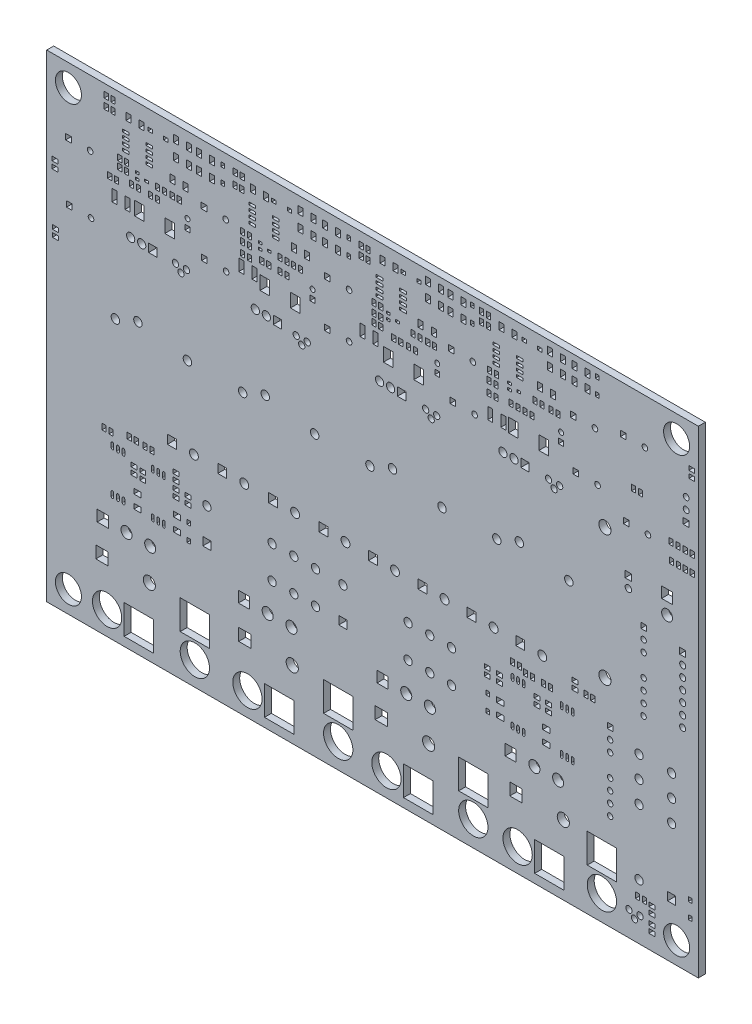
SolidWorks part; units mm, degrees
ref_plane "Plan de face" through (0, 0, 0) normal (0, 0, 1) x (1, 0, 0)
ref_plane "Plan de dessus" through (0, 0, 0) normal (0, 1, 0) x (1, 0, 0)
ref_plane "Plan de droite" through (0, 0, 0) normal (1, 0, 0) x (0, 0, -1)
sketch "Model" plane through (0, 0, 0) normal (0, 0, 1) x (1, 0, 0)
  line L0 (113.3, -20.025) -> (115.5, -20.025)
  line L1 (115.5, -20.025) -> (115.5, -23.175)
  line L2 (115.5, -23.175) -> (113.3, -23.175)
  line L3 (113.3, -23.175) -> (113.3, -20.025)
  line L4 (106.3, -20.025) -> (108.5, -20.025)
  line L5 (108.5, -20.025) -> (108.5, -23.175)
  line L6 (108.5, -23.175) -> (106.3, -23.175)
  line L7 (106.3, -23.175) -> (106.3, -20.025)
  line L8 (84.5, -20.325) -> (86.7, -20.325)
  line L9 (86.7, -20.325) -> (86.7, -23.475)
  line L10 (86.7, -23.475) -> (84.5, -23.475)
  line L11 (84.5, -23.475) -> (84.5, -20.325)
  line L12 (77.5, -20.325) -> (79.7, -20.325)
  line L13 (79.7, -20.325) -> (79.7, -23.475)
  line L14 (79.7, -23.475) -> (77.5, -23.475)
  line L15 (77.5, -23.475) -> (77.5, -20.325)
  line L16 (56.1, -20.225) -> (58.3, -20.225)
  line L17 (58.3, -20.225) -> (58.3, -23.375)
  line L18 (58.3, -23.375) -> (56.1, -23.375)
  line L19 (56.1, -23.375) -> (56.1, -20.225)
  line L20 (49.1, -20.225) -> (51.3, -20.225)
  line L21 (51.3, -20.225) -> (51.3, -23.375)
  line L22 (51.3, -23.375) -> (49.1, -23.375)
  line L23 (49.1, -23.375) -> (49.1, -20.225)
  line L24 (27.2, -19.825) -> (29.4, -19.825)
  line L25 (29.4, -19.825) -> (29.4, -22.975)
  line L26 (29.4, -22.975) -> (27.2, -22.975)
  line L27 (27.2, -22.975) -> (27.2, -19.825)
  line L28 (20.2, -19.825) -> (22.4, -19.825)
  line L29 (22.4, -19.825) -> (22.4, -22.975)
  line L30 (22.4, -22.975) -> (20.2, -22.975)
  line L31 (20.2, -22.975) -> (20.2, -19.825)
  line L32 (17.425, -7.595) -> (17.425, -6.995)
  line L33 (17.425, -6.995) -> (18.975, -6.995)
  line L34 (18.975, -6.995) -> (18.975, -7.595)
  line L35 (18.975, -7.595) -> (17.425, -7.595)
  line L36 (17.425, -8.865) -> (17.425, -8.265)
  line L37 (17.425, -8.265) -> (18.975, -8.265)
  line L38 (18.975, -8.265) -> (18.975, -8.865)
  line L39 (18.975, -8.865) -> (17.425, -8.865)
  line L40 (17.425, -10.135) -> (17.425, -9.535)
  line L41 (17.425, -9.535) -> (18.975, -9.535)
  line L42 (18.975, -9.535) -> (18.975, -10.135)
  line L43 (18.975, -10.135) -> (17.425, -10.135)
  line L44 (17.425, -11.405) -> (17.425, -10.805)
  line L45 (17.425, -10.805) -> (18.975, -10.805)
  line L46 (18.975, -10.805) -> (18.975, -11.405)
  line L47 (18.975, -11.405) -> (17.425, -11.405)
  line L48 (22.825, -11.405) -> (22.825, -10.805)
  line L49 (22.825, -10.805) -> (24.375, -10.805)
  line L50 (24.375, -10.805) -> (24.375, -11.405)
  line L51 (24.375, -11.405) -> (22.825, -11.405)
  line L52 (22.825, -10.135) -> (22.825, -9.535)
  line L53 (22.825, -9.535) -> (24.375, -9.535)
  line L54 (24.375, -9.535) -> (24.375, -10.135)
  line L55 (24.375, -10.135) -> (22.825, -10.135)
  line L56 (22.825, -8.865) -> (22.825, -8.265)
  line L57 (22.825, -8.265) -> (24.375, -8.265)
  line L58 (24.375, -8.265) -> (24.375, -8.865)
  line L59 (24.375, -8.865) -> (22.825, -8.865)
  line L60 (22.825, -7.595) -> (22.825, -6.995)
  line L61 (22.825, -6.995) -> (24.375, -6.995)
  line L62 (24.375, -6.995) -> (24.375, -7.595)
  line L63 (24.375, -7.595) -> (22.825, -7.595)
  line L64 (102.725, -7.395) -> (102.725, -6.795)
  line L65 (102.725, -6.795) -> (104.275, -6.795)
  line L66 (104.275, -6.795) -> (104.275, -7.395)
  line L67 (104.275, -7.395) -> (102.725, -7.395)
  line L68 (102.725, -8.665) -> (102.725, -8.065)
  line L69 (102.725, -8.065) -> (104.275, -8.065)
  line L70 (104.275, -8.065) -> (104.275, -8.665)
  line L71 (104.275, -8.665) -> (102.725, -8.665)
  line L72 (102.725, -9.935) -> (102.725, -9.335)
  line L73 (102.725, -9.335) -> (104.275, -9.335)
  line L74 (104.275, -9.335) -> (104.275, -9.935)
  line L75 (104.275, -9.935) -> (102.725, -9.935)
  line L76 (102.725, -11.205) -> (102.725, -10.605)
  line L77 (102.725, -10.605) -> (104.275, -10.605)
  line L78 (104.275, -10.605) -> (104.275, -11.205)
  line L79 (104.275, -11.205) -> (102.725, -11.205)
  line L80 (108.125, -11.205) -> (108.125, -10.605)
  line L81 (108.125, -10.605) -> (109.675, -10.605)
  line L82 (109.675, -10.605) -> (109.675, -11.205)
  line L83 (109.675, -11.205) -> (108.125, -11.205)
  line L84 (108.125, -9.935) -> (108.125, -9.335)
  line L85 (108.125, -9.335) -> (109.675, -9.335)
  line L86 (109.675, -9.335) -> (109.675, -9.935)
  line L87 (109.675, -9.935) -> (108.125, -9.935)
  line L88 (108.125, -8.665) -> (108.125, -8.065)
  line L89 (108.125, -8.065) -> (109.675, -8.065)
  line L90 (109.675, -8.065) -> (109.675, -8.665)
  line L91 (109.675, -8.665) -> (108.125, -8.665)
  line L92 (108.125, -7.395) -> (108.125, -6.795)
  line L93 (108.125, -6.795) -> (109.675, -6.795)
  line L94 (109.675, -6.795) -> (109.675, -7.395)
  line L95 (109.675, -7.395) -> (108.125, -7.395)
  line L96 (75.825, -7.395) -> (75.825, -6.795)
  line L97 (75.825, -6.795) -> (77.375, -6.795)
  line L98 (77.375, -6.795) -> (77.375, -7.395)
  line L99 (77.375, -7.395) -> (75.825, -7.395)
  line L100 (75.825, -8.665) -> (75.825, -8.065)
  line L101 (75.825, -8.065) -> (77.375, -8.065)
  line L102 (77.375, -8.065) -> (77.375, -8.665)
  line L103 (77.375, -8.665) -> (75.825, -8.665)
  line L104 (75.825, -9.935) -> (75.825, -9.335)
  line L105 (75.825, -9.335) -> (77.375, -9.335)
  line L106 (77.375, -9.335) -> (77.375, -9.935)
  line L107 (77.375, -9.935) -> (75.825, -9.935)
  line L108 (75.825, -11.205) -> (75.825, -10.605)
  line L109 (75.825, -10.605) -> (77.375, -10.605)
  line L110 (77.375, -10.605) -> (77.375, -11.205)
  line L111 (77.375, -11.205) -> (75.825, -11.205)
  line L112 (81.225, -11.205) -> (81.225, -10.605)
  line L113 (81.225, -10.605) -> (82.775, -10.605)
  line L114 (82.775, -10.605) -> (82.775, -11.205)
  line L115 (82.775, -11.205) -> (81.225, -11.205)
  line L116 (81.225, -9.935) -> (81.225, -9.335)
  line L117 (81.225, -9.335) -> (82.775, -9.335)
  line L118 (82.775, -9.335) -> (82.775, -9.935)
  line L119 (82.775, -9.935) -> (81.225, -9.935)
  line L120 (81.225, -8.665) -> (81.225, -8.065)
  line L121 (81.225, -8.065) -> (82.775, -8.065)
  line L122 (82.775, -8.065) -> (82.775, -8.665)
  line L123 (82.775, -8.665) -> (81.225, -8.665)
  line L124 (81.225, -7.395) -> (81.225, -6.795)
  line L125 (81.225, -6.795) -> (82.775, -6.795)
  line L126 (82.775, -6.795) -> (82.775, -7.395)
  line L127 (82.775, -7.395) -> (81.225, -7.395)
  line L128 (46.525, -7.595) -> (46.525, -6.995)
  line L129 (46.525, -6.995) -> (48.075, -6.995)
  line L130 (48.075, -6.995) -> (48.075, -7.595)
  line L131 (48.075, -7.595) -> (46.525, -7.595)
  line L132 (46.525, -8.865) -> (46.525, -8.265)
  line L133 (46.525, -8.265) -> (48.075, -8.265)
  line L134 (48.075, -8.265) -> (48.075, -8.865)
  line L135 (48.075, -8.865) -> (46.525, -8.865)
  line L136 (46.525, -10.135) -> (46.525, -9.535)
  line L137 (46.525, -9.535) -> (48.075, -9.535)
  line L138 (48.075, -9.535) -> (48.075, -10.135)
  line L139 (48.075, -10.135) -> (46.525, -10.135)
  line L140 (46.525, -11.405) -> (46.525, -10.805)
  line L141 (46.525, -10.805) -> (48.075, -10.805)
  line L142 (48.075, -10.805) -> (48.075, -11.405)
  line L143 (48.075, -11.405) -> (46.525, -11.405)
  line L144 (51.925, -11.405) -> (51.925, -10.805)
  line L145 (51.925, -10.805) -> (53.475, -10.805)
  line L146 (53.475, -10.805) -> (53.475, -11.405)
  line L147 (53.475, -11.405) -> (51.925, -11.405)
  line L148 (51.925, -10.135) -> (51.925, -9.535)
  line L149 (51.925, -9.535) -> (53.475, -9.535)
  line L150 (53.475, -9.535) -> (53.475, -10.135)
  line L151 (53.475, -10.135) -> (51.925, -10.135)
  line L152 (51.925, -8.865) -> (51.925, -8.265)
  line L153 (51.925, -8.265) -> (53.475, -8.265)
  line L154 (53.475, -8.265) -> (53.475, -8.865)
  line L155 (53.475, -8.865) -> (51.925, -8.865)
  line L156 (51.925, -7.595) -> (51.925, -6.995)
  line L157 (51.925, -6.995) -> (53.475, -6.995)
  line L158 (53.475, -6.995) -> (53.475, -7.595)
  line L159 (53.475, -7.595) -> (51.925, -7.595)
  line L160 (147.875, -21.275) -> (146.525, -21.275)
  line L161 (146.525, -21.275) -> (146.525, -19.925)
  line L162 (146.525, -19.925) -> (147.875, -19.925)
  line L163 (147.875, -19.925) -> (147.875, -21.275)
  line L164 (144.925, -29.325) -> (145.875, -29.325)
  line L165 (145.875, -29.325) -> (145.875, -30.675)
  line L166 (145.875, -30.675) -> (144.925, -30.675)
  line L167 (144.925, -30.675) -> (144.925, -29.325)
  line L168 (143.325, -29.325) -> (144.275, -29.325)
  line L169 (144.275, -29.325) -> (144.275, -30.675)
  line L170 (144.275, -30.675) -> (143.325, -30.675)
  line L171 (143.325, -30.675) -> (143.325, -29.325)
  line L172 (144.825, -25.525) -> (145.775, -25.525)
  line L173 (145.775, -25.525) -> (145.775, -26.875)
  line L174 (145.775, -26.875) -> (144.825, -26.875)
  line L175 (144.825, -26.875) -> (144.825, -25.525)
  line L176 (143.225, -25.525) -> (144.175, -25.525)
  line L177 (144.175, -25.525) -> (144.175, -26.875)
  line L178 (144.175, -26.875) -> (143.225, -26.875)
  line L179 (143.225, -26.875) -> (143.225, -25.525)
  line L180 (133.15, -37.15) -> (134.65, -37.15)
  line L181 (134.65, -37.15) -> (134.65, -38.65)
  line L182 (134.65, -38.65) -> (133.15, -38.65)
  line L183 (133.15, -38.65) -> (133.15, -37.15)
  line L184 (145.7, -46.2) -> (147.1, -46.2)
  line L185 (147.1, -46.2) -> (147.1, -47.6)
  line L186 (147.1, -47.6) -> (145.7, -47.6)
  line L187 (145.7, -47.6) -> (145.7, -46.2)
  line L188 (141.55, -36.05) -> (144.05, -36.05)
  line L189 (144.05, -36.05) -> (144.05, -38.55)
  line L190 (144.05, -38.55) -> (141.55, -38.55)
  line L191 (141.55, -38.55) -> (141.55, -36.05)
  line L192 (129.075, -70.725) -> (129.075, -69.475)
  line L193 (129.075, -69.475) -> (130.325, -69.475)
  line L194 (130.325, -69.475) -> (130.325, -70.725)
  line L195 (130.325, -70.725) -> (129.075, -70.725)
  line L196 (136.775, -46.925) -> (136.775, -45.675)
  line L197 (136.775, -45.675) -> (138.025, -45.675)
  line L198 (138.025, -45.675) -> (138.025, -46.925)
  line L199 (138.025, -46.925) -> (136.775, -46.925)
  line L200 (120.77, -71.925) -> (120.77, -70.975)
  line L201 (121.37, -70.975) -> (121.37, -71.925)
  line L202 (119.5, -71.925) -> (119.5, -70.975)
  line L203 (120.1, -70.975) -> (120.1, -71.925)
  line L204 (118.23, -71.925) -> (118.23, -70.975)
  line L205 (118.83, -70.975) -> (118.83, -71.925)
  line L206 (118.23, -81.625) -> (118.23, -80.675)
  line L207 (118.83, -80.675) -> (118.83, -81.625)
  line L208 (119.5, -81.625) -> (119.5, -80.675)
  line L209 (120.1, -80.675) -> (120.1, -81.625)
  line L210 (120.77, -81.625) -> (120.77, -80.675)
  line L211 (121.37, -80.675) -> (121.37, -81.625)
  line L212 (109.47, -71.925) -> (109.47, -70.975)
  line L213 (110.07, -70.975) -> (110.07, -71.925)
  line L214 (108.2, -71.925) -> (108.2, -70.975)
  line L215 (108.8, -70.975) -> (108.8, -71.925)
  line L216 (106.93, -71.925) -> (106.93, -70.975)
  line L217 (107.53, -70.975) -> (107.53, -71.925)
  line L218 (106.93, -81.625) -> (106.93, -80.675)
  line L219 (107.53, -80.675) -> (107.53, -81.625)
  line L220 (108.2, -81.625) -> (108.2, -80.675)
  line L221 (108.8, -80.675) -> (108.8, -81.625)
  line L222 (109.47, -81.625) -> (109.47, -80.675)
  line L223 (110.07, -80.675) -> (110.07, -81.625)
  line L224 (26.67, -71.825) -> (26.67, -70.875)
  line L225 (27.27, -70.875) -> (27.27, -71.825)
  line L226 (25.4, -71.825) -> (25.4, -70.875)
  line L227 (26, -70.875) -> (26, -71.825)
  line L228 (24.13, -71.825) -> (24.13, -70.875)
  line L229 (24.73, -70.875) -> (24.73, -71.825)
  line L230 (24.13, -81.525) -> (24.13, -80.575)
  line L231 (24.73, -80.575) -> (24.73, -81.525)
  line L232 (25.4, -81.525) -> (25.4, -80.575)
  line L233 (26, -80.575) -> (26, -81.525)
  line L234 (26.67, -81.525) -> (26.67, -80.575)
  line L235 (27.27, -80.575) -> (27.27, -81.525)
  line L236 (17.37, -71.825) -> (17.37, -70.875)
  line L237 (17.97, -70.875) -> (17.97, -71.825)
  line L238 (16.1, -71.825) -> (16.1, -70.875)
  line L239 (16.7, -70.875) -> (16.7, -71.825)
  line L240 (14.83, -71.825) -> (14.83, -70.875)
  line L241 (15.43, -70.875) -> (15.43, -71.825)
  line L242 (14.83, -81.525) -> (14.83, -80.575)
  line L243 (15.43, -80.575) -> (15.43, -81.525)
  line L244 (16.1, -81.525) -> (16.1, -80.575)
  line L245 (16.7, -80.575) -> (16.7, -81.525)
  line L246 (17.37, -81.525) -> (17.37, -80.575)
  line L247 (17.97, -80.575) -> (17.97, -81.525)
  line L248 (109.4, -95.4) -> (106.6, -95.4)
  line L249 (106.6, -95.4) -> (106.6, -92.6)
  line L250 (106.6, -92.6) -> (109.4, -92.6)
  line L251 (109.4, -92.6) -> (109.4, -95.4)
  line L252 (78.4, -95.7) -> (75.6, -95.7)
  line L253 (75.6, -95.7) -> (75.6, -92.9)
  line L254 (75.6, -92.9) -> (78.4, -92.9)
  line L255 (78.4, -92.9) -> (78.4, -95.7)
  line L256 (14.1, -95.8) -> (11.3, -95.8)
  line L257 (11.3, -95.8) -> (11.3, -93)
  line L258 (11.3, -93) -> (14.1, -93)
  line L259 (14.1, -93) -> (14.1, -95.8)
  line L260 (47, -95.8) -> (44.2, -95.8)
  line L261 (44.2, -95.8) -> (44.2, -93)
  line L262 (44.2, -93) -> (47, -93)
  line L263 (47, -93) -> (47, -95.8)
  line L264 (108.075, -87.975) -> (105.525, -87.975)
  line L265 (105.525, -87.975) -> (105.525, -85.425)
  line L266 (105.525, -85.425) -> (108.075, -85.425)
  line L267 (108.075, -85.425) -> (108.075, -87.975)
  line L268 (78.575, -88.175) -> (76.025, -88.175)
  line L269 (76.025, -88.175) -> (76.025, -85.625)
  line L270 (76.025, -85.625) -> (78.575, -85.625)
  line L271 (78.575, -85.625) -> (78.575, -88.175)
  line L272 (46.675, -88.175) -> (44.125, -88.175)
  line L273 (44.125, -88.175) -> (44.125, -85.625)
  line L274 (44.125, -85.625) -> (46.675, -85.625)
  line L275 (46.675, -85.625) -> (46.675, -88.175)
  line L276 (14.175, -88.275) -> (11.625, -88.275)
  line L277 (11.625, -88.275) -> (11.625, -85.725)
  line L278 (11.625, -85.725) -> (14.175, -85.725)
  line L279 (14.175, -85.725) -> (14.175, -88.275)
  line L280 (124.425, -93.525) -> (131.175, -93.525)
  line L281 (131.175, -93.525) -> (131.175, -100.275)
  line L282 (131.175, -100.275) -> (124.425, -100.275)
  line L283 (124.425, -100.275) -> (124.425, -93.525)
  line L284 (119.075, -101.225) -> (119.075, -107.975)
  line L285 (119.075, -107.975) -> (112.325, -107.975)
  line L286 (112.325, -107.975) -> (112.325, -101.225)
  line L287 (112.325, -101.225) -> (119.075, -101.225)
  line L288 (94.825, -93.525) -> (101.575, -93.525)
  line L289 (101.575, -93.525) -> (101.575, -100.275)
  line L290 (101.575, -100.275) -> (94.825, -100.275)
  line L291 (94.825, -100.275) -> (94.825, -93.525)
  line L292 (88.875, -101.225) -> (88.875, -107.975)
  line L293 (88.875, -107.975) -> (82.125, -107.975)
  line L294 (82.125, -107.975) -> (82.125, -101.225)
  line L295 (82.125, -101.225) -> (88.875, -101.225)
  line L296 (56.875, -101.225) -> (56.875, -107.975)
  line L297 (56.875, -107.975) -> (50.125, -107.975)
  line L298 (50.125, -107.975) -> (50.125, -101.225)
  line L299 (50.125, -101.225) -> (56.875, -101.225)
  line L300 (63.725, -93.625) -> (70.475, -93.625)
  line L301 (70.475, -93.625) -> (70.475, -100.375)
  line L302 (70.475, -100.375) -> (63.725, -100.375)
  line L303 (63.725, -100.375) -> (63.725, -93.625)
  line L304 (24.575, -101.225) -> (24.575, -107.975)
  line L305 (24.575, -107.975) -> (17.825, -107.975)
  line L306 (17.825, -107.975) -> (17.825, -101.225)
  line L307 (17.825, -101.225) -> (24.575, -101.225)
  line L308 (30.725, -93.825) -> (37.475, -93.825)
  line L309 (37.475, -93.825) -> (37.475, -100.575)
  line L310 (37.475, -100.575) -> (30.725, -100.575)
  line L311 (30.725, -100.575) -> (30.725, -93.825)
  line L312 (120.55, -12.95) -> (120.55, -11.65)
  line L313 (120.55, -11.65) -> (121.85, -11.65)
  line L314 (121.85, -11.65) -> (121.85, -12.95)
  line L315 (121.85, -12.95) -> (120.55, -12.95)
  line L316 (121.15, -23.95) -> (121.15, -22.65)
  line L317 (121.15, -22.65) -> (122.45, -22.65)
  line L318 (122.45, -22.65) -> (122.45, -23.95)
  line L319 (122.45, -23.95) -> (121.15, -23.95)
  line L320 (92.45, -13.75) -> (92.45, -12.45)
  line L321 (92.45, -12.45) -> (93.75, -12.45)
  line L322 (93.75, -12.45) -> (93.75, -13.75)
  line L323 (93.75, -13.75) -> (92.45, -13.75)
  line L324 (92.85, -24.05) -> (92.85, -22.75)
  line L325 (92.85, -22.75) -> (94.15, -22.75)
  line L326 (94.15, -22.75) -> (94.15, -24.05)
  line L327 (94.15, -24.05) -> (92.85, -24.05)
  line L328 (63.95, -13.65) -> (63.95, -12.35)
  line L329 (63.95, -12.35) -> (65.25, -12.35)
  line L330 (65.25, -12.35) -> (65.25, -13.65)
  line L331 (65.25, -13.65) -> (63.95, -13.65)
  line L332 (63.95, -23.95) -> (63.95, -22.65)
  line L333 (63.95, -22.65) -> (65.25, -22.65)
  line L334 (65.25, -22.65) -> (65.25, -23.95)
  line L335 (65.25, -23.95) -> (63.95, -23.95)
  line L336 (35.55, -13.85) -> (35.55, -12.55)
  line L337 (35.55, -12.55) -> (36.85, -12.55)
  line L338 (36.85, -12.55) -> (36.85, -13.85)
  line L339 (36.85, -13.85) -> (35.55, -13.85)
  line L340 (35.65, -24.15) -> (35.65, -22.85)
  line L341 (35.65, -22.85) -> (36.95, -22.85)
  line L342 (36.95, -22.85) -> (36.95, -24.15)
  line L343 (36.95, -24.15) -> (35.65, -24.15)
  line L344 (115.825, -80.225) -> (115.825, -81.375)
  line L345 (115.825, -81.375) -> (114.175, -81.375)
  line L346 (114.175, -81.375) -> (114.175, -80.225)
  line L347 (114.175, -80.225) -> (115.825, -80.225)
  line L348 (115.825, -77.225) -> (115.825, -78.375)
  line L349 (115.825, -78.375) -> (114.175, -78.375)
  line L350 (114.175, -78.375) -> (114.175, -77.225)
  line L351 (114.175, -77.225) -> (115.825, -77.225)
  line L352 (105.225, -80.125) -> (105.225, -81.275)
  line L353 (105.225, -81.275) -> (103.575, -81.275)
  line L354 (103.575, -81.275) -> (103.575, -80.125)
  line L355 (103.575, -80.125) -> (105.225, -80.125)
  line L356 (105.225, -77.125) -> (105.225, -78.275)
  line L357 (105.225, -78.275) -> (103.575, -78.275)
  line L358 (103.575, -78.275) -> (103.575, -77.125)
  line L359 (103.575, -77.125) -> (105.225, -77.125)
  line L360 (30.825, -80.325) -> (30.825, -81.475)
  line L361 (30.825, -81.475) -> (29.175, -81.475)
  line L362 (29.175, -81.475) -> (29.175, -80.325)
  line L363 (29.175, -80.325) -> (30.825, -80.325)
  line L364 (30.825, -77.325) -> (30.825, -78.475)
  line L365 (30.825, -78.475) -> (29.175, -78.475)
  line L366 (29.175, -78.475) -> (29.175, -77.325)
  line L367 (29.175, -77.325) -> (30.825, -77.325)
  line L368 (21.725, -80.325) -> (21.725, -81.475)
  line L369 (21.725, -81.475) -> (20.075, -81.475)
  line L370 (20.075, -81.475) -> (20.075, -80.325)
  line L371 (20.075, -80.325) -> (21.725, -80.325)
  line L372 (21.725, -77.325) -> (21.725, -78.475)
  line L373 (21.725, -78.475) -> (20.075, -78.475)
  line L374 (20.075, -78.475) -> (20.075, -77.325)
  line L375 (20.075, -77.325) -> (21.725, -77.325)
  line L376 (105.275, -3.725) -> (104.125, -3.725)
  line L377 (104.125, -3.725) -> (104.125, -2.075)
  line L378 (104.125, -2.075) -> (105.275, -2.075)
  line L379 (105.275, -2.075) -> (105.275, -3.725)
  line L380 (108.275, -3.725) -> (107.125, -3.725)
  line L381 (107.125, -3.725) -> (107.125, -2.075)
  line L382 (107.125, -2.075) -> (108.275, -2.075)
  line L383 (108.275, -2.075) -> (108.275, -3.725)
  line L384 (77.875, -4.125) -> (76.725, -4.125)
  line L385 (76.725, -4.125) -> (76.725, -2.475)
  line L386 (76.725, -2.475) -> (77.875, -2.475)
  line L387 (77.875, -2.475) -> (77.875, -4.125)
  line L388 (80.875, -4.125) -> (79.725, -4.125)
  line L389 (79.725, -4.125) -> (79.725, -2.475)
  line L390 (79.725, -2.475) -> (80.875, -2.475)
  line L391 (80.875, -2.475) -> (80.875, -4.125)
  line L392 (115.925, -9.575) -> (117.075, -9.575)
  line L393 (117.075, -9.575) -> (117.075, -11.225)
  line L394 (117.075, -11.225) -> (115.925, -11.225)
  line L395 (115.925, -11.225) -> (115.925, -9.575)
  line L396 (112.925, -9.575) -> (114.075, -9.575)
  line L397 (114.075, -9.575) -> (114.075, -11.225)
  line L398 (114.075, -11.225) -> (112.925, -11.225)
  line L399 (112.925, -11.225) -> (112.925, -9.575)
  line L400 (88.525, -10.875) -> (89.675, -10.875)
  line L401 (89.675, -10.875) -> (89.675, -12.525)
  line L402 (89.675, -12.525) -> (88.525, -12.525)
  line L403 (88.525, -12.525) -> (88.525, -10.875)
  line L404 (85.525, -10.875) -> (86.675, -10.875)
  line L405 (86.675, -10.875) -> (86.675, -12.525)
  line L406 (86.675, -12.525) -> (85.525, -12.525)
  line L407 (85.525, -12.525) -> (85.525, -10.875)
  line L408 (118.225, -1.375) -> (119.375, -1.375)
  line L409 (119.375, -1.375) -> (119.375, -3.025)
  line L410 (119.375, -3.025) -> (118.225, -3.025)
  line L411 (118.225, -3.025) -> (118.225, -1.375)
  line L412 (115.225, -1.375) -> (116.375, -1.375)
  line L413 (116.375, -1.375) -> (116.375, -3.025)
  line L414 (116.375, -3.025) -> (115.225, -3.025)
  line L415 (115.225, -3.025) -> (115.225, -1.375)
  line L416 (123.925, -1.375) -> (125.075, -1.375)
  line L417 (125.075, -1.375) -> (125.075, -3.025)
  line L418 (125.075, -3.025) -> (123.925, -3.025)
  line L419 (123.925, -3.025) -> (123.925, -1.375)
  line L420 (120.925, -1.375) -> (122.075, -1.375)
  line L421 (122.075, -1.375) -> (122.075, -3.025)
  line L422 (122.075, -3.025) -> (120.925, -3.025)
  line L423 (120.925, -3.025) -> (120.925, -1.375)
  line L424 (116.375, -6.125) -> (115.225, -6.125)
  line L425 (115.225, -6.125) -> (115.225, -4.475)
  line L426 (115.225, -4.475) -> (116.375, -4.475)
  line L427 (116.375, -4.475) -> (116.375, -6.125)
  line L428 (119.375, -6.125) -> (118.225, -6.125)
  line L429 (118.225, -6.125) -> (118.225, -4.475)
  line L430 (118.225, -4.475) -> (119.375, -4.475)
  line L431 (119.375, -4.475) -> (119.375, -6.125)
  line L432 (122.075, -6.125) -> (120.925, -6.125)
  line L433 (120.925, -6.125) -> (120.925, -4.475)
  line L434 (120.925, -4.475) -> (122.075, -4.475)
  line L435 (122.075, -4.475) -> (122.075, -6.125)
  line L436 (125.075, -6.125) -> (123.925, -6.125)
  line L437 (123.925, -6.125) -> (123.925, -4.475)
  line L438 (123.925, -4.475) -> (125.075, -4.475)
  line L439 (125.075, -4.475) -> (125.075, -6.125)
  line L440 (90.225, -1.475) -> (91.375, -1.475)
  line L441 (91.375, -1.475) -> (91.375, -3.125)
  line L442 (91.375, -3.125) -> (90.225, -3.125)
  line L443 (90.225, -3.125) -> (90.225, -1.475)
  line L444 (87.225, -1.475) -> (88.375, -1.475)
  line L445 (88.375, -1.475) -> (88.375, -3.125)
  line L446 (88.375, -3.125) -> (87.225, -3.125)
  line L447 (87.225, -3.125) -> (87.225, -1.475)
  line L448 (95.325, -1.475) -> (96.475, -1.475)
  line L449 (96.475, -1.475) -> (96.475, -3.125)
  line L450 (96.475, -3.125) -> (95.325, -3.125)
  line L451 (95.325, -3.125) -> (95.325, -1.475)
  line L452 (92.325, -1.475) -> (93.475, -1.475)
  line L453 (93.475, -1.475) -> (93.475, -3.125)
  line L454 (93.475, -3.125) -> (92.325, -3.125)
  line L455 (92.325, -3.125) -> (92.325, -1.475)
  line L456 (93.475, -6.525) -> (92.325, -6.525)
  line L457 (92.325, -6.525) -> (92.325, -4.875)
  line L458 (92.325, -4.875) -> (93.475, -4.875)
  line L459 (93.475, -4.875) -> (93.475, -6.525)
  line L460 (96.475, -6.525) -> (95.325, -6.525)
  line L461 (95.325, -6.525) -> (95.325, -4.875)
  line L462 (95.325, -4.875) -> (96.475, -4.875)
  line L463 (96.475, -4.875) -> (96.475, -6.525)
  line L464 (88.375, -6.525) -> (87.225, -6.525)
  line L465 (87.225, -6.525) -> (87.225, -4.875)
  line L466 (87.225, -4.875) -> (88.375, -4.875)
  line L467 (88.375, -4.875) -> (88.375, -6.525)
  line L468 (91.375, -6.525) -> (90.225, -6.525)
  line L469 (90.225, -6.525) -> (90.225, -4.875)
  line L470 (90.225, -4.875) -> (91.375, -4.875)
  line L471 (91.375, -4.875) -> (91.375, -6.525)
  line L472 (48.075, -4.825) -> (46.925, -4.825)
  line L473 (46.925, -4.825) -> (46.925, -3.175)
  line L474 (46.925, -3.175) -> (48.075, -3.175)
  line L475 (48.075, -3.175) -> (48.075, -4.825)
  line L476 (51.075, -4.825) -> (49.925, -4.825)
  line L477 (49.925, -4.825) -> (49.925, -3.175)
  line L478 (49.925, -3.175) -> (51.075, -3.175)
  line L479 (51.075, -3.175) -> (51.075, -4.825)
  line L480 (60.825, -2.075) -> (61.975, -2.075)
  line L481 (61.975, -2.075) -> (61.975, -3.725)
  line L482 (61.975, -3.725) -> (60.825, -3.725)
  line L483 (60.825, -3.725) -> (60.825, -2.075)
  line L484 (57.825, -2.075) -> (58.975, -2.075)
  line L485 (58.975, -2.075) -> (58.975, -3.725)
  line L486 (58.975, -3.725) -> (57.825, -3.725)
  line L487 (57.825, -3.725) -> (57.825, -2.075)
  line L488 (66.525, -2.075) -> (67.675, -2.075)
  line L489 (67.675, -2.075) -> (67.675, -3.725)
  line L490 (67.675, -3.725) -> (66.525, -3.725)
  line L491 (66.525, -3.725) -> (66.525, -2.075)
  line L492 (63.525, -2.075) -> (64.675, -2.075)
  line L493 (64.675, -2.075) -> (64.675, -3.725)
  line L494 (64.675, -3.725) -> (63.525, -3.725)
  line L495 (63.525, -3.725) -> (63.525, -2.075)
  line L496 (58.975, -7.225) -> (57.825, -7.225)
  line L497 (57.825, -7.225) -> (57.825, -5.575)
  line L498 (57.825, -5.575) -> (58.975, -5.575)
  line L499 (58.975, -5.575) -> (58.975, -7.225)
  line L500 (61.975, -7.225) -> (60.825, -7.225)
  line L501 (60.825, -7.225) -> (60.825, -5.575)
  line L502 (60.825, -5.575) -> (61.975, -5.575)
  line L503 (61.975, -5.575) -> (61.975, -7.225)
  line L504 (64.675, -7.225) -> (63.525, -7.225)
  line L505 (63.525, -7.225) -> (63.525, -5.575)
  line L506 (63.525, -5.575) -> (64.675, -5.575)
  line L507 (64.675, -5.575) -> (64.675, -7.225)
  line L508 (67.675, -7.225) -> (66.525, -7.225)
  line L509 (66.525, -7.225) -> (66.525, -5.575)
  line L510 (66.525, -5.575) -> (67.675, -5.575)
  line L511 (67.675, -5.575) -> (67.675, -7.225)
  line L512 (59.325, -10.175) -> (60.475, -10.175)
  line L513 (60.475, -10.175) -> (60.475, -11.825)
  line L514 (60.475, -11.825) -> (59.325, -11.825)
  line L515 (59.325, -11.825) -> (59.325, -10.175)
  line L516 (56.325, -10.175) -> (57.475, -10.175)
  line L517 (57.475, -10.175) -> (57.475, -11.825)
  line L518 (57.475, -11.825) -> (56.325, -11.825)
  line L519 (56.325, -11.825) -> (56.325, -10.175)
  line L520 (32.225, -2.175) -> (33.375, -2.175)
  line L521 (33.375, -2.175) -> (33.375, -3.825)
  line L522 (33.375, -3.825) -> (32.225, -3.825)
  line L523 (32.225, -3.825) -> (32.225, -2.175)
  line L524 (29.225, -2.175) -> (30.375, -2.175)
  line L525 (30.375, -2.175) -> (30.375, -3.825)
  line L526 (30.375, -3.825) -> (29.225, -3.825)
  line L527 (29.225, -3.825) -> (29.225, -2.175)
  line L528 (37.525, -2.175) -> (38.675, -2.175)
  line L529 (38.675, -2.175) -> (38.675, -3.825)
  line L530 (38.675, -3.825) -> (37.525, -3.825)
  line L531 (37.525, -3.825) -> (37.525, -2.175)
  line L532 (34.525, -2.175) -> (35.675, -2.175)
  line L533 (35.675, -2.175) -> (35.675, -3.825)
  line L534 (35.675, -3.825) -> (34.525, -3.825)
  line L535 (34.525, -3.825) -> (34.525, -2.175)
  line L536 (35.675, -7.425) -> (34.525, -7.425)
  line L537 (34.525, -7.425) -> (34.525, -5.775)
  line L538 (34.525, -5.775) -> (35.675, -5.775)
  line L539 (35.675, -5.775) -> (35.675, -7.425)
  line L540 (38.675, -7.425) -> (37.525, -7.425)
  line L541 (37.525, -7.425) -> (37.525, -5.775)
  line L542 (37.525, -5.775) -> (38.675, -5.775)
  line L543 (38.675, -5.775) -> (38.675, -7.425)
  line L544 (30.375, -7.425) -> (29.225, -7.425)
  line L545 (29.225, -7.425) -> (29.225, -5.775)
  line L546 (29.225, -5.775) -> (30.375, -5.775)
  line L547 (30.375, -5.775) -> (30.375, -7.425)
  line L548 (33.375, -7.425) -> (32.225, -7.425)
  line L549 (32.225, -7.425) -> (32.225, -5.775)
  line L550 (32.225, -5.775) -> (33.375, -5.775)
  line L551 (33.375, -5.775) -> (33.375, -7.425)
  line L552 (31.325, -10.475) -> (32.475, -10.475)
  line L553 (32.475, -10.475) -> (32.475, -12.125)
  line L554 (32.475, -12.125) -> (31.325, -12.125)
  line L555 (31.325, -12.125) -> (31.325, -10.475)
  line L556 (28.325, -10.475) -> (29.475, -10.475)
  line L557 (29.475, -10.475) -> (29.475, -12.125)
  line L558 (29.475, -12.125) -> (28.325, -12.125)
  line L559 (28.325, -12.125) -> (28.325, -10.475)
  line L560 (19.375, -4.925) -> (18.225, -4.925)
  line L561 (18.225, -4.925) -> (18.225, -3.275)
  line L562 (18.225, -3.275) -> (19.375, -3.275)
  line L563 (19.375, -3.275) -> (19.375, -4.925)
  line L564 (22.375, -4.925) -> (21.225, -4.925)
  line L565 (21.225, -4.925) -> (21.225, -3.275)
  line L566 (21.225, -3.275) -> (22.375, -3.275)
  line L567 (22.375, -3.275) -> (22.375, -4.925)
  line L568 (132.75, -28.05) -> (132.75, -26.75)
  line L569 (132.75, -26.75) -> (134.05, -26.75)
  line L570 (134.05, -26.75) -> (134.05, -28.05)
  line L571 (134.05, -28.05) -> (132.75, -28.05)
  line L572 (132.05, -11.05) -> (132.05, -9.75)
  line L573 (132.05, -9.75) -> (133.35, -9.75)
  line L574 (133.35, -9.75) -> (133.35, -11.05)
  line L575 (133.35, -11.05) -> (132.05, -11.05)
  line L576 (4.55, -29.05) -> (4.55, -27.75)
  line L577 (4.55, -27.75) -> (5.85, -27.75)
  line L578 (5.85, -27.75) -> (5.85, -29.05)
  line L579 (5.85, -29.05) -> (4.55, -29.05)
  line L580 (4.35, -15.75) -> (4.35, -14.45)
  line L581 (4.35, -14.45) -> (5.65, -14.45)
  line L582 (5.65, -14.45) -> (5.65, -15.75)
  line L583 (5.65, -15.75) -> (4.35, -15.75)
  line L584 (118.975, -19.575) -> (117.825, -19.575)
  line L585 (117.825, -19.575) -> (117.825, -18.425)
  line L586 (117.825, -18.425) -> (118.975, -18.425)
  line L587 (118.975, -18.425) -> (118.975, -19.575)
  line L588 (90.475, -20.075) -> (89.325, -20.075)
  line L589 (89.325, -20.075) -> (89.325, -18.925)
  line L590 (89.325, -18.925) -> (90.475, -18.925)
  line L591 (90.475, -18.925) -> (90.475, -20.075)
  line L592 (61.775, -19.675) -> (60.625, -19.675)
  line L593 (60.625, -19.675) -> (60.625, -18.525)
  line L594 (60.625, -18.525) -> (61.775, -18.525)
  line L595 (61.775, -18.525) -> (61.775, -19.675)
  line L596 (32.975, -19.975) -> (31.825, -19.975)
  line L597 (31.825, -19.975) -> (31.825, -18.825)
  line L598 (31.825, -18.825) -> (32.975, -18.825)
  line L599 (32.975, -18.825) -> (32.975, -19.975)
  line L600 (104.525, -20.25) -> (105.675, -20.25)
  line L601 (105.675, -20.25) -> (105.675, -22.95)
  line L602 (105.675, -22.95) -> (104.525, -22.95)
  line L603 (104.525, -22.95) -> (104.525, -20.25)
  line L604 (101.525, -20.25) -> (102.675, -20.25)
  line L605 (102.675, -20.25) -> (102.675, -22.95)
  line L606 (102.675, -22.95) -> (101.525, -22.95)
  line L607 (101.525, -22.95) -> (101.525, -20.25)
  line L608 (75.125, -18.35) -> (76.275, -18.35)
  line L609 (76.275, -18.35) -> (76.275, -21.05)
  line L610 (76.275, -21.05) -> (75.125, -21.05)
  line L611 (75.125, -21.05) -> (75.125, -18.35)
  line L612 (72.125, -18.35) -> (73.275, -18.35)
  line L613 (73.275, -18.35) -> (73.275, -21.05)
  line L614 (73.275, -21.05) -> (72.125, -21.05)
  line L615 (72.125, -21.05) -> (72.125, -18.35)
  line L616 (47.225, -19.35) -> (48.375, -19.35)
  line L617 (48.375, -19.35) -> (48.375, -22.05)
  line L618 (48.375, -22.05) -> (47.225, -22.05)
  line L619 (47.225, -22.05) -> (47.225, -19.35)
  line L620 (44.225, -19.35) -> (45.375, -19.35)
  line L621 (45.375, -19.35) -> (45.375, -22.05)
  line L622 (45.375, -22.05) -> (44.225, -22.05)
  line L623 (44.225, -22.05) -> (44.225, -19.35)
  line L624 (18.025, -20.05) -> (19.175, -20.05)
  line L625 (19.175, -20.05) -> (19.175, -22.75)
  line L626 (19.175, -22.75) -> (18.025, -22.75)
  line L627 (18.025, -22.75) -> (18.025, -20.05)
  line L628 (15.025, -20.05) -> (16.175, -20.05)
  line L629 (16.175, -20.05) -> (16.175, -22.75)
  line L630 (16.175, -22.75) -> (15.025, -22.75)
  line L631 (15.025, -22.75) -> (15.025, -20.05)
  line L632 (147.475, -30.675) -> (146.525, -30.675)
  line L633 (146.525, -30.675) -> (146.525, -29.325)
  line L634 (146.525, -29.325) -> (147.475, -29.325)
  line L635 (147.475, -29.325) -> (147.475, -30.675)
  line L636 (149.075, -30.675) -> (148.125, -30.675)
  line L637 (148.125, -30.675) -> (148.125, -29.325)
  line L638 (148.125, -29.325) -> (149.075, -29.325)
  line L639 (149.075, -29.325) -> (149.075, -30.675)
  line L640 (136.475, -101.375) -> (135.525, -101.375)
  line L641 (135.525, -101.375) -> (135.525, -100.025)
  line L642 (135.525, -100.025) -> (136.475, -100.025)
  line L643 (136.475, -100.025) -> (136.475, -101.375)
  line L644 (138.075, -101.375) -> (137.125, -101.375)
  line L645 (137.125, -101.375) -> (137.125, -100.025)
  line L646 (137.125, -100.025) -> (138.075, -100.025)
  line L647 (138.075, -100.025) -> (138.075, -101.375)
  line L648 (114.875, -69.775) -> (113.925, -69.775)
  line L649 (113.925, -69.775) -> (113.925, -68.425)
  line L650 (113.925, -68.425) -> (114.875, -68.425)
  line L651 (114.875, -68.425) -> (114.875, -69.775)
  line L652 (116.475, -69.775) -> (115.525, -69.775)
  line L653 (115.525, -69.775) -> (115.525, -68.425)
  line L654 (115.525, -68.425) -> (116.475, -68.425)
  line L655 (116.475, -68.425) -> (116.475, -69.775)
  line L656 (107.675, -69.075) -> (106.725, -69.075)
  line L657 (106.725, -69.075) -> (106.725, -67.725)
  line L658 (106.725, -67.725) -> (107.675, -67.725)
  line L659 (107.675, -67.725) -> (107.675, -69.075)
  line L660 (109.275, -69.075) -> (108.325, -69.075)
  line L661 (108.325, -69.075) -> (108.325, -67.725)
  line L662 (108.325, -67.725) -> (109.275, -67.725)
  line L663 (109.275, -67.725) -> (109.275, -69.075)
  line L664 (23.075, -68.375) -> (22.125, -68.375)
  line L665 (22.125, -68.375) -> (22.125, -67.025)
  line L666 (22.125, -67.025) -> (23.075, -67.025)
  line L667 (23.075, -67.025) -> (23.075, -68.375)
  line L668 (24.675, -68.375) -> (23.725, -68.375)
  line L669 (23.725, -68.375) -> (23.725, -67.025)
  line L670 (23.725, -67.025) -> (24.675, -67.025)
  line L671 (24.675, -67.025) -> (24.675, -68.375)
  line L672 (13.675, -69.375) -> (12.725, -69.375)
  line L673 (12.725, -69.375) -> (12.725, -68.025)
  line L674 (12.725, -68.025) -> (13.675, -68.025)
  line L675 (13.675, -68.025) -> (13.675, -69.375)
  line L676 (15.275, -69.375) -> (14.325, -69.375)
  line L677 (14.325, -69.375) -> (14.325, -68.025)
  line L678 (14.325, -68.025) -> (15.275, -68.025)
  line L679 (15.275, -68.025) -> (15.275, -69.375)
  line L680 (124.575, -67.075) -> (123.625, -67.075)
  line L681 (123.625, -67.075) -> (123.625, -65.725)
  line L682 (123.625, -65.725) -> (124.575, -65.725)
  line L683 (124.575, -65.725) -> (124.575, -67.075)
  line L684 (126.175, -67.075) -> (125.225, -67.075)
  line L685 (125.225, -67.075) -> (125.225, -65.725)
  line L686 (125.225, -65.725) -> (126.175, -65.725)
  line L687 (126.175, -65.725) -> (126.175, -67.075)
  line L688 (111.325, -68.425) -> (112.275, -68.425)
  line L689 (112.275, -68.425) -> (112.275, -69.775)
  line L690 (112.275, -69.775) -> (111.325, -69.775)
  line L691 (111.325, -69.775) -> (111.325, -68.425)
  line L692 (109.725, -68.425) -> (110.675, -68.425)
  line L693 (110.675, -68.425) -> (110.675, -69.775)
  line L694 (110.675, -69.775) -> (109.725, -69.775)
  line L695 (109.725, -69.775) -> (109.725, -68.425)
  line L696 (30.475, -70.525) -> (30.475, -71.475)
  line L697 (30.475, -71.475) -> (29.125, -71.475)
  line L698 (29.125, -71.475) -> (29.125, -70.525)
  line L699 (29.125, -70.525) -> (30.475, -70.525)
  line L700 (30.475, -68.925) -> (30.475, -69.875)
  line L701 (30.475, -69.875) -> (29.125, -69.875)
  line L702 (29.125, -69.875) -> (29.125, -68.925)
  line L703 (29.125, -68.925) -> (30.475, -68.925)
  line L704 (20.125, -66.925) -> (21.075, -66.925)
  line L705 (21.075, -66.925) -> (21.075, -68.275)
  line L706 (21.075, -68.275) -> (20.125, -68.275)
  line L707 (20.125, -68.275) -> (20.125, -66.925)
  line L708 (18.525, -66.925) -> (19.475, -66.925)
  line L709 (19.475, -66.925) -> (19.475, -68.275)
  line L710 (19.475, -68.275) -> (18.525, -68.275)
  line L711 (18.525, -68.275) -> (18.525, -66.925)
  line L712 (147.475, -26.875) -> (146.525, -26.875)
  line L713 (146.525, -26.875) -> (146.525, -25.525)
  line L714 (146.525, -25.525) -> (147.475, -25.525)
  line L715 (147.475, -25.525) -> (147.475, -26.875)
  line L716 (149.075, -26.875) -> (148.125, -26.875)
  line L717 (148.125, -26.875) -> (148.125, -25.525)
  line L718 (148.125, -25.525) -> (149.075, -25.525)
  line L719 (149.075, -25.525) -> (149.075, -26.875)
  line L720 (139.975, -105.825) -> (139.975, -106.775)
  line L721 (139.975, -106.775) -> (138.625, -106.775)
  line L722 (138.625, -106.775) -> (138.625, -105.825)
  line L723 (138.625, -105.825) -> (139.975, -105.825)
  line L724 (139.975, -104.225) -> (139.975, -105.175)
  line L725 (139.975, -105.175) -> (138.625, -105.175)
  line L726 (138.625, -105.175) -> (138.625, -104.225)
  line L727 (138.625, -104.225) -> (139.975, -104.225)
  line L728 (139.975, -102.125) -> (139.975, -103.075)
  line L729 (139.975, -103.075) -> (138.625, -103.075)
  line L730 (138.625, -103.075) -> (138.625, -102.125)
  line L731 (138.625, -102.125) -> (139.975, -102.125)
  line L732 (139.975, -100.525) -> (139.975, -101.475)
  line L733 (139.975, -101.475) -> (138.625, -101.475)
  line L734 (138.625, -101.475) -> (138.625, -100.525)
  line L735 (138.625, -100.525) -> (139.975, -100.525)
  line L736 (120.925, -65.475) -> (120.925, -64.525)
  line L737 (120.925, -64.525) -> (122.275, -64.525)
  line L738 (122.275, -64.525) -> (122.275, -65.475)
  line L739 (122.275, -65.475) -> (120.925, -65.475)
  line L740 (120.925, -67.075) -> (120.925, -66.125)
  line L741 (120.925, -66.125) -> (122.275, -66.125)
  line L742 (122.275, -66.125) -> (122.275, -67.075)
  line L743 (122.275, -67.075) -> (120.925, -67.075)
  line L744 (114.825, -73.075) -> (114.825, -72.125)
  line L745 (114.825, -72.125) -> (116.175, -72.125)
  line L746 (116.175, -72.125) -> (116.175, -73.075)
  line L747 (116.175, -73.075) -> (114.825, -73.075)
  line L748 (114.825, -74.675) -> (114.825, -73.725)
  line L749 (114.825, -73.725) -> (116.175, -73.725)
  line L750 (116.175, -73.725) -> (116.175, -74.675)
  line L751 (116.175, -74.675) -> (114.825, -74.675)
  line L752 (112.225, -73.075) -> (112.225, -72.125)
  line L753 (112.225, -72.125) -> (113.575, -72.125)
  line L754 (113.575, -72.125) -> (113.575, -73.075)
  line L755 (113.575, -73.075) -> (112.225, -73.075)
  line L756 (112.225, -74.675) -> (112.225, -73.725)
  line L757 (112.225, -73.725) -> (113.575, -73.725)
  line L758 (113.575, -73.725) -> (113.575, -74.675)
  line L759 (113.575, -74.675) -> (112.225, -74.675)
  line L760 (103.525, -72.875) -> (103.525, -71.925)
  line L761 (103.525, -71.925) -> (104.875, -71.925)
  line L762 (104.875, -71.925) -> (104.875, -72.875)
  line L763 (104.875, -72.875) -> (103.525, -72.875)
  line L764 (103.525, -74.475) -> (103.525, -73.525)
  line L765 (103.525, -73.525) -> (104.875, -73.525)
  line L766 (104.875, -73.525) -> (104.875, -74.475)
  line L767 (104.875, -74.475) -> (103.525, -74.475)
  line L768 (100.725, -72.875) -> (100.725, -71.925)
  line L769 (100.725, -71.925) -> (102.075, -71.925)
  line L770 (102.075, -71.925) -> (102.075, -72.875)
  line L771 (102.075, -72.875) -> (100.725, -72.875)
  line L772 (100.725, -74.475) -> (100.725, -73.525)
  line L773 (100.725, -73.525) -> (102.075, -73.525)
  line L774 (102.075, -73.525) -> (102.075, -74.475)
  line L775 (102.075, -74.475) -> (100.725, -74.475)
  line L776 (31.825, -73.175) -> (31.825, -72.225)
  line L777 (31.825, -72.225) -> (33.175, -72.225)
  line L778 (33.175, -72.225) -> (33.175, -73.175)
  line L779 (33.175, -73.175) -> (31.825, -73.175)
  line L780 (31.825, -74.775) -> (31.825, -73.825)
  line L781 (31.825, -73.825) -> (33.175, -73.825)
  line L782 (33.175, -73.825) -> (33.175, -74.775)
  line L783 (33.175, -74.775) -> (31.825, -74.775)
  line L784 (29.125, -73.175) -> (29.125, -72.225)
  line L785 (29.125, -72.225) -> (30.475, -72.225)
  line L786 (30.475, -72.225) -> (30.475, -73.175)
  line L787 (30.475, -73.175) -> (29.125, -73.175)
  line L788 (29.125, -74.775) -> (29.125, -73.825)
  line L789 (29.125, -73.825) -> (30.475, -73.825)
  line L790 (30.475, -73.825) -> (30.475, -74.775)
  line L791 (30.475, -74.775) -> (29.125, -74.775)
  line L792 (21.425, -73.475) -> (21.425, -72.525)
  line L793 (21.425, -72.525) -> (22.775, -72.525)
  line L794 (22.775, -72.525) -> (22.775, -73.475)
  line L795 (22.775, -73.475) -> (21.425, -73.475)
  line L796 (21.425, -75.075) -> (21.425, -74.125)
  line L797 (21.425, -74.125) -> (22.775, -74.125)
  line L798 (22.775, -74.125) -> (22.775, -75.075)
  line L799 (22.775, -75.075) -> (21.425, -75.075)
  line L800 (19.425, -73.375) -> (19.425, -72.425)
  line L801 (19.425, -72.425) -> (20.775, -72.425)
  line L802 (20.775, -72.425) -> (20.775, -73.375)
  line L803 (20.775, -73.375) -> (19.425, -73.375)
  line L804 (19.425, -74.975) -> (19.425, -74.025)
  line L805 (19.425, -74.025) -> (20.775, -74.025)
  line L806 (20.775, -74.025) -> (20.775, -74.975)
  line L807 (20.775, -74.975) -> (19.425, -74.975)
  line L808 (136.225, -19.225) -> (137.175, -19.225)
  line L809 (137.175, -19.225) -> (137.175, -20.575)
  line L810 (137.175, -20.575) -> (136.225, -20.575)
  line L811 (136.225, -20.575) -> (136.225, -19.225)
  line L812 (134.625, -19.225) -> (135.575, -19.225)
  line L813 (135.575, -19.225) -> (135.575, -20.575)
  line L814 (135.575, -20.575) -> (134.625, -20.575)
  line L815 (134.625, -20.575) -> (134.625, -19.225)
  line L816 (147.825, -9.875) -> (147.825, -8.925)
  line L817 (147.825, -8.925) -> (149.175, -8.925)
  line L818 (149.175, -8.925) -> (149.175, -9.875)
  line L819 (149.175, -9.875) -> (147.825, -9.875)
  line L820 (147.825, -11.475) -> (147.825, -10.525)
  line L821 (147.825, -10.525) -> (149.175, -10.525)
  line L822 (149.175, -10.525) -> (149.175, -11.475)
  line L823 (149.175, -11.475) -> (147.825, -11.475)
  line L824 (76.425, -14.125) -> (77.375, -14.125)
  line L825 (77.375, -14.125) -> (77.375, -15.475)
  line L826 (77.375, -15.475) -> (76.425, -15.475)
  line L827 (76.425, -15.475) -> (76.425, -14.125)
  line L828 (74.825, -14.125) -> (75.775, -14.125)
  line L829 (75.775, -14.125) -> (75.775, -15.475)
  line L830 (75.775, -15.475) -> (74.825, -15.475)
  line L831 (74.825, -15.475) -> (74.825, -14.125)
  line L832 (102.375, -13.575) -> (101.425, -13.575)
  line L833 (101.425, -13.575) -> (101.425, -12.225)
  line L834 (101.425, -12.225) -> (102.375, -12.225)
  line L835 (102.375, -12.225) -> (102.375, -13.575)
  line L836 (103.975, -13.575) -> (103.025, -13.575)
  line L837 (103.025, -13.575) -> (103.025, -12.225)
  line L838 (103.025, -12.225) -> (103.975, -12.225)
  line L839 (103.975, -12.225) -> (103.975, -13.575)
  line L840 (75.775, -13.375) -> (74.825, -13.375)
  line L841 (74.825, -13.375) -> (74.825, -12.025)
  line L842 (74.825, -12.025) -> (75.775, -12.025)
  line L843 (75.775, -12.025) -> (75.775, -13.375)
  line L844 (77.375, -13.375) -> (76.425, -13.375)
  line L845 (76.425, -13.375) -> (76.425, -12.025)
  line L846 (76.425, -12.025) -> (77.375, -12.025)
  line L847 (77.375, -12.025) -> (77.375, -13.375)
  line L848 (100.575, -4.875) -> (99.625, -4.875)
  line L849 (99.625, -4.875) -> (99.625, -3.525)
  line L850 (99.625, -3.525) -> (100.575, -3.525)
  line L851 (100.575, -3.525) -> (100.575, -4.875)
  line L852 (102.175, -4.875) -> (101.225, -4.875)
  line L853 (101.225, -4.875) -> (101.225, -3.525)
  line L854 (101.225, -3.525) -> (102.175, -3.525)
  line L855 (102.175, -3.525) -> (102.175, -4.875)
  line L856 (101.225, -1.425) -> (102.175, -1.425)
  line L857 (102.175, -1.425) -> (102.175, -2.775)
  line L858 (102.175, -2.775) -> (101.225, -2.775)
  line L859 (101.225, -2.775) -> (101.225, -1.425)
  line L860 (99.625, -1.425) -> (100.575, -1.425)
  line L861 (100.575, -1.425) -> (100.575, -2.775)
  line L862 (100.575, -2.775) -> (99.625, -2.775)
  line L863 (99.625, -2.775) -> (99.625, -1.425)
  line L864 (72.875, -5.575) -> (71.925, -5.575)
  line L865 (71.925, -5.575) -> (71.925, -4.225)
  line L866 (71.925, -4.225) -> (72.875, -4.225)
  line L867 (72.875, -4.225) -> (72.875, -5.575)
  line L868 (74.475, -5.575) -> (73.525, -5.575)
  line L869 (73.525, -5.575) -> (73.525, -4.225)
  line L870 (73.525, -4.225) -> (74.475, -4.225)
  line L871 (74.475, -4.225) -> (74.475, -5.575)
  line L872 (73.525, -2.125) -> (74.475, -2.125)
  line L873 (74.475, -2.125) -> (74.475, -3.475)
  line L874 (74.475, -3.475) -> (73.525, -3.475)
  line L875 (73.525, -3.475) -> (73.525, -2.125)
  line L876 (71.925, -2.125) -> (72.875, -2.125)
  line L877 (72.875, -2.125) -> (72.875, -3.475)
  line L878 (72.875, -3.475) -> (71.925, -3.475)
  line L879 (71.925, -3.475) -> (71.925, -2.125)
  line L880 (102.925, -16.825) -> (103.875, -16.825)
  line L881 (103.875, -16.825) -> (103.875, -18.175)
  line L882 (103.875, -18.175) -> (102.925, -18.175)
  line L883 (102.925, -18.175) -> (102.925, -16.825)
  line L884 (101.325, -16.825) -> (102.275, -16.825)
  line L885 (102.275, -16.825) -> (102.275, -18.175)
  line L886 (102.275, -18.175) -> (101.325, -18.175)
  line L887 (101.325, -18.175) -> (101.325, -16.825)
  line L888 (108.025, -16.325) -> (108.975, -16.325)
  line L889 (108.975, -16.325) -> (108.975, -17.675)
  line L890 (108.975, -17.675) -> (108.025, -17.675)
  line L891 (108.025, -17.675) -> (108.025, -16.325)
  line L892 (106.425, -16.325) -> (107.375, -16.325)
  line L893 (107.375, -16.325) -> (107.375, -17.675)
  line L894 (107.375, -17.675) -> (106.425, -17.675)
  line L895 (106.425, -17.675) -> (106.425, -16.325)
  line L896 (110.575, -17.675) -> (109.625, -17.675)
  line L897 (109.625, -17.675) -> (109.625, -16.325)
  line L898 (109.625, -16.325) -> (110.575, -16.325)
  line L899 (110.575, -16.325) -> (110.575, -17.675)
  line L900 (112.175, -17.675) -> (111.225, -17.675)
  line L901 (111.225, -17.675) -> (111.225, -16.325)
  line L902 (111.225, -16.325) -> (112.175, -16.325)
  line L903 (112.175, -16.325) -> (112.175, -17.675)
  line L904 (76.425, -16.025) -> (77.375, -16.025)
  line L905 (77.375, -16.025) -> (77.375, -17.375)
  line L906 (77.375, -17.375) -> (76.425, -17.375)
  line L907 (76.425, -17.375) -> (76.425, -16.025)
  line L908 (74.825, -16.025) -> (75.775, -16.025)
  line L909 (75.775, -16.025) -> (75.775, -17.375)
  line L910 (75.775, -17.375) -> (74.825, -17.375)
  line L911 (74.825, -17.375) -> (74.825, -16.025)
  line L912 (81.025, -16.825) -> (81.975, -16.825)
  line L913 (81.975, -16.825) -> (81.975, -18.175)
  line L914 (81.975, -18.175) -> (81.025, -18.175)
  line L915 (81.025, -18.175) -> (81.025, -16.825)
  line L916 (79.425, -16.825) -> (80.375, -16.825)
  line L917 (80.375, -16.825) -> (80.375, -18.175)
  line L918 (80.375, -18.175) -> (79.425, -18.175)
  line L919 (79.425, -18.175) -> (79.425, -16.825)
  line L920 (84.425, -16.825) -> (85.375, -16.825)
  line L921 (85.375, -16.825) -> (85.375, -18.175)
  line L922 (85.375, -18.175) -> (84.425, -18.175)
  line L923 (84.425, -18.175) -> (84.425, -16.825)
  line L924 (82.825, -16.825) -> (83.775, -16.825)
  line L925 (83.775, -16.825) -> (83.775, -18.175)
  line L926 (83.775, -18.175) -> (82.825, -18.175)
  line L927 (82.825, -18.175) -> (82.825, -16.825)
  line L928 (116.575, -14.375) -> (115.625, -14.375)
  line L929 (115.625, -14.375) -> (115.625, -13.025)
  line L930 (115.625, -13.025) -> (116.575, -13.025)
  line L931 (116.575, -13.025) -> (116.575, -14.375)
  line L932 (118.175, -14.375) -> (117.225, -14.375)
  line L933 (117.225, -14.375) -> (117.225, -13.025)
  line L934 (117.225, -13.025) -> (118.175, -13.025)
  line L935 (118.175, -13.025) -> (118.175, -14.375)
  line L936 (112.875, -14.375) -> (111.925, -14.375)
  line L937 (111.925, -14.375) -> (111.925, -13.025)
  line L938 (111.925, -13.025) -> (112.875, -13.025)
  line L939 (112.875, -13.025) -> (112.875, -14.375)
  line L940 (114.475, -14.375) -> (113.525, -14.375)
  line L941 (113.525, -14.375) -> (113.525, -13.025)
  line L942 (113.525, -13.025) -> (114.475, -13.025)
  line L943 (114.475, -13.025) -> (114.475, -14.375)
  line L944 (88.175, -15.075) -> (87.225, -15.075)
  line L945 (87.225, -15.075) -> (87.225, -13.725)
  line L946 (87.225, -13.725) -> (88.175, -13.725)
  line L947 (88.175, -13.725) -> (88.175, -15.075)
  line L948 (89.775, -15.075) -> (88.825, -15.075)
  line L949 (88.825, -15.075) -> (88.825, -13.725)
  line L950 (88.825, -13.725) -> (89.775, -13.725)
  line L951 (89.775, -13.725) -> (89.775, -15.075)
  line L952 (84.775, -15.075) -> (83.825, -15.075)
  line L953 (83.825, -15.075) -> (83.825, -13.725)
  line L954 (83.825, -13.725) -> (84.775, -13.725)
  line L955 (84.775, -13.725) -> (84.775, -15.075)
  line L956 (86.375, -15.075) -> (85.425, -15.075)
  line L957 (85.425, -15.075) -> (85.425, -13.725)
  line L958 (85.425, -13.725) -> (86.375, -13.725)
  line L959 (86.375, -13.725) -> (86.375, -15.075)
  line L960 (102.925, -14.325) -> (103.875, -14.325)
  line L961 (103.875, -14.325) -> (103.875, -15.675)
  line L962 (103.875, -15.675) -> (102.925, -15.675)
  line L963 (102.925, -15.675) -> (102.925, -14.325)
  line L964 (101.325, -14.325) -> (102.275, -14.325)
  line L965 (102.275, -14.325) -> (102.275, -15.675)
  line L966 (102.275, -15.675) -> (101.325, -15.675)
  line L967 (101.325, -15.675) -> (101.325, -14.325)
  line L968 (2.675, -35.725) -> (2.675, -36.675)
  line L969 (2.675, -36.675) -> (1.325, -36.675)
  line L970 (1.325, -36.675) -> (1.325, -35.725)
  line L971 (1.325, -35.725) -> (2.675, -35.725)
  line L972 (2.675, -34.125) -> (2.675, -35.075)
  line L973 (2.675, -35.075) -> (1.325, -35.075)
  line L974 (1.325, -35.075) -> (1.325, -34.125)
  line L975 (1.325, -34.125) -> (2.675, -34.125)
  line L976 (45.575, -14.375) -> (44.625, -14.375)
  line L977 (44.625, -14.375) -> (44.625, -13.025)
  line L978 (44.625, -13.025) -> (45.575, -13.025)
  line L979 (45.575, -13.025) -> (45.575, -14.375)
  line L980 (47.175, -14.375) -> (46.225, -14.375)
  line L981 (46.225, -14.375) -> (46.225, -13.025)
  line L982 (46.225, -13.025) -> (47.175, -13.025)
  line L983 (47.175, -13.025) -> (47.175, -14.375)
  line L984 (44.525, -2.025) -> (45.475, -2.025)
  line L985 (45.475, -2.025) -> (45.475, -3.375)
  line L986 (45.475, -3.375) -> (44.525, -3.375)
  line L987 (44.525, -3.375) -> (44.525, -2.025)
  line L988 (42.925, -2.025) -> (43.875, -2.025)
  line L989 (43.875, -2.025) -> (43.875, -3.375)
  line L990 (43.875, -3.375) -> (42.925, -3.375)
  line L991 (42.925, -3.375) -> (42.925, -2.025)
  line L992 (43.775, -5.975) -> (42.825, -5.975)
  line L993 (42.825, -5.975) -> (42.825, -4.625)
  line L994 (42.825, -4.625) -> (43.775, -4.625)
  line L995 (43.775, -4.625) -> (43.775, -5.975)
  line L996 (45.375, -5.975) -> (44.425, -5.975)
  line L997 (44.425, -5.975) -> (44.425, -4.625)
  line L998 (44.425, -4.625) -> (45.375, -4.625)
  line L999 (45.375, -4.625) -> (45.375, -5.975)
  line L1000 (57.275, -15.175) -> (56.325, -15.175)
  line L1001 (56.325, -15.175) -> (56.325, -13.825)
  line L1002 (56.325, -13.825) -> (57.275, -13.825)
  line L1003 (57.275, -13.825) -> (57.275, -15.175)
  line L1004 (58.875, -15.175) -> (57.925, -15.175)
  line L1005 (57.925, -15.175) -> (57.925, -13.825)
  line L1006 (57.925, -13.825) -> (58.875, -13.825)
  line L1007 (58.875, -13.825) -> (58.875, -15.175)
  line L1008 (54.175, -15.175) -> (53.225, -15.175)
  line L1009 (53.225, -15.175) -> (53.225, -13.825)
  line L1010 (53.225, -13.825) -> (54.175, -13.825)
  line L1011 (54.175, -13.825) -> (54.175, -15.175)
  line L1012 (55.775, -15.175) -> (54.825, -15.175)
  line L1013 (54.825, -15.175) -> (54.825, -13.825)
  line L1014 (54.825, -13.825) -> (55.775, -13.825)
  line L1015 (55.775, -13.825) -> (55.775, -15.175)
  line L1016 (46.225, -17.425) -> (47.175, -17.425)
  line L1017 (47.175, -17.425) -> (47.175, -18.775)
  line L1018 (47.175, -18.775) -> (46.225, -18.775)
  line L1019 (46.225, -18.775) -> (46.225, -17.425)
  line L1020 (44.625, -17.425) -> (45.575, -17.425)
  line L1021 (45.575, -17.425) -> (45.575, -18.775)
  line L1022 (45.575, -18.775) -> (44.625, -18.775)
  line L1023 (44.625, -18.775) -> (44.625, -17.425)
  line L1024 (50.625, -16.625) -> (51.575, -16.625)
  line L1025 (51.575, -16.625) -> (51.575, -17.975)
  line L1026 (51.575, -17.975) -> (50.625, -17.975)
  line L1027 (50.625, -17.975) -> (50.625, -16.625)
  line L1028 (49.025, -16.625) -> (49.975, -16.625)
  line L1029 (49.975, -16.625) -> (49.975, -17.975)
  line L1030 (49.975, -17.975) -> (49.025, -17.975)
  line L1031 (49.025, -17.975) -> (49.025, -16.625)
  line L1032 (54.825, -16.625) -> (55.775, -16.625)
  line L1033 (55.775, -16.625) -> (55.775, -17.975)
  line L1034 (55.775, -17.975) -> (54.825, -17.975)
  line L1035 (54.825, -17.975) -> (54.825, -16.625)
  line L1036 (53.225, -16.625) -> (54.175, -16.625)
  line L1037 (54.175, -16.625) -> (54.175, -17.975)
  line L1038 (54.175, -17.975) -> (53.225, -17.975)
  line L1039 (53.225, -17.975) -> (53.225, -16.625)
  line L1040 (46.225, -15.025) -> (47.175, -15.025)
  line L1041 (47.175, -15.025) -> (47.175, -16.375)
  line L1042 (47.175, -16.375) -> (46.225, -16.375)
  line L1043 (46.225, -16.375) -> (46.225, -15.025)
  line L1044 (44.625, -15.025) -> (45.575, -15.025)
  line L1045 (45.575, -15.025) -> (45.575, -16.375)
  line L1046 (45.575, -16.375) -> (44.625, -16.375)
  line L1047 (44.625, -16.375) -> (44.625, -15.025)
  line L1048 (17.275, -13.875) -> (16.325, -13.875)
  line L1049 (16.325, -13.875) -> (16.325, -12.525)
  line L1050 (16.325, -12.525) -> (17.275, -12.525)
  line L1051 (17.275, -12.525) -> (17.275, -13.875)
  line L1052 (18.875, -13.875) -> (17.925, -13.875)
  line L1053 (17.925, -13.875) -> (17.925, -12.525)
  line L1054 (17.925, -12.525) -> (18.875, -12.525)
  line L1055 (18.875, -12.525) -> (18.875, -13.875)
  line L1056 (29.375, -15.275) -> (28.425, -15.275)
  line L1057 (28.425, -15.275) -> (28.425, -13.925)
  line L1058 (28.425, -13.925) -> (29.375, -13.925)
  line L1059 (29.375, -13.925) -> (29.375, -15.275)
  line L1060 (30.975, -15.275) -> (30.025, -15.275)
  line L1061 (30.025, -15.275) -> (30.025, -13.925)
  line L1062 (30.025, -13.925) -> (30.975, -13.925)
  line L1063 (30.975, -13.925) -> (30.975, -15.275)
  line L1064 (25.975, -15.275) -> (25.025, -15.275)
  line L1065 (25.025, -15.275) -> (25.025, -13.925)
  line L1066 (25.025, -13.925) -> (25.975, -13.925)
  line L1067 (25.975, -13.925) -> (25.975, -15.275)
  line L1068 (27.575, -15.275) -> (26.625, -15.275)
  line L1069 (26.625, -15.275) -> (26.625, -13.925)
  line L1070 (26.625, -13.925) -> (27.575, -13.925)
  line L1071 (27.575, -13.925) -> (27.575, -15.275)
  line L1072 (14.175, -5.175) -> (13.225, -5.175)
  line L1073 (13.225, -5.175) -> (13.225, -3.825)
  line L1074 (13.225, -3.825) -> (14.175, -3.825)
  line L1075 (14.175, -3.825) -> (14.175, -5.175)
  line L1076 (15.775, -5.175) -> (14.825, -5.175)
  line L1077 (14.825, -5.175) -> (14.825, -3.825)
  line L1078 (14.825, -3.825) -> (15.775, -3.825)
  line L1079 (15.775, -3.825) -> (15.775, -5.175)
  line L1080 (14.825, -1.625) -> (15.775, -1.625)
  line L1081 (15.775, -1.625) -> (15.775, -2.975)
  line L1082 (15.775, -2.975) -> (14.825, -2.975)
  line L1083 (14.825, -2.975) -> (14.825, -1.625)
  line L1084 (13.225, -1.625) -> (14.175, -1.625)
  line L1085 (14.175, -1.625) -> (14.175, -2.975)
  line L1086 (14.175, -2.975) -> (13.225, -2.975)
  line L1087 (13.225, -2.975) -> (13.225, -1.625)
  line L1088 (2.575, -22.125) -> (2.575, -23.075)
  line L1089 (2.575, -23.075) -> (1.225, -23.075)
  line L1090 (1.225, -23.075) -> (1.225, -22.125)
  line L1091 (1.225, -22.125) -> (2.575, -22.125)
  line L1092 (2.575, -20.525) -> (2.575, -21.475)
  line L1093 (2.575, -21.475) -> (1.225, -21.475)
  line L1094 (1.225, -21.475) -> (1.225, -20.525)
  line L1095 (1.225, -20.525) -> (2.575, -20.525)
  line L1096 (17.925, -14.325) -> (18.875, -14.325)
  line L1097 (18.875, -14.325) -> (18.875, -15.675)
  line L1098 (18.875, -15.675) -> (17.925, -15.675)
  line L1099 (17.925, -15.675) -> (17.925, -14.325)
  line L1100 (16.325, -14.325) -> (17.275, -14.325)
  line L1101 (17.275, -14.325) -> (17.275, -15.675)
  line L1102 (17.275, -15.675) -> (16.325, -15.675)
  line L1103 (16.325, -15.675) -> (16.325, -14.325)
  line L1104 (15.625, -17.225) -> (16.575, -17.225)
  line L1105 (16.575, -17.225) -> (16.575, -18.575)
  line L1106 (16.575, -18.575) -> (15.625, -18.575)
  line L1107 (15.625, -18.575) -> (15.625, -17.225)
  line L1108 (14.025, -17.225) -> (14.975, -17.225)
  line L1109 (14.975, -17.225) -> (14.975, -18.575)
  line L1110 (14.975, -18.575) -> (14.025, -18.575)
  line L1111 (14.025, -18.575) -> (14.025, -17.225)
  line L1112 (20.625, -16.325) -> (21.575, -16.325)
  line L1113 (21.575, -16.325) -> (21.575, -17.675)
  line L1114 (21.575, -17.675) -> (20.625, -17.675)
  line L1115 (20.625, -17.675) -> (20.625, -16.325)
  line L1116 (19.025, -16.325) -> (19.975, -16.325)
  line L1117 (19.975, -16.325) -> (19.975, -17.675)
  line L1118 (19.975, -17.675) -> (19.025, -17.675)
  line L1119 (19.025, -17.675) -> (19.025, -16.325)
  line L1120 (25.025, -16.325) -> (25.975, -16.325)
  line L1121 (25.975, -16.325) -> (25.975, -17.675)
  line L1122 (25.975, -17.675) -> (25.025, -17.675)
  line L1123 (25.025, -17.675) -> (25.025, -16.325)
  line L1124 (23.425, -16.325) -> (24.375, -16.325)
  line L1125 (24.375, -16.325) -> (24.375, -17.675)
  line L1126 (24.375, -17.675) -> (23.425, -17.675)
  line L1127 (23.425, -17.675) -> (23.425, -16.325)
  line L1128 (106.125, -13.425) -> (106.125, -12.875)
  line L1129 (106.125, -12.875) -> (106.975, -12.875)
  line L1130 (106.975, -12.875) -> (106.975, -13.425)
  line L1131 (106.975, -13.425) -> (106.125, -13.425)
  line L1132 (106.125, -14.725) -> (106.125, -14.175)
  line L1133 (106.125, -14.175) -> (106.975, -14.175)
  line L1134 (106.975, -14.175) -> (106.975, -14.725)
  line L1135 (106.975, -14.725) -> (106.125, -14.725)
  line L1136 (108.225, -14.075) -> (108.225, -13.525)
  line L1137 (108.225, -13.525) -> (109.075, -13.525)
  line L1138 (109.075, -13.525) -> (109.075, -14.075)
  line L1139 (109.075, -14.075) -> (108.225, -14.075)
  line L1140 (78.225, -13.425) -> (78.225, -12.875)
  line L1141 (78.225, -12.875) -> (79.075, -12.875)
  line L1142 (79.075, -12.875) -> (79.075, -13.425)
  line L1143 (79.075, -13.425) -> (78.225, -13.425)
  line L1144 (78.225, -14.725) -> (78.225, -14.175)
  line L1145 (78.225, -14.175) -> (79.075, -14.175)
  line L1146 (79.075, -14.175) -> (79.075, -14.725)
  line L1147 (79.075, -14.725) -> (78.225, -14.725)
  line L1148 (80.325, -14.075) -> (80.325, -13.525)
  line L1149 (80.325, -13.525) -> (81.175, -13.525)
  line L1150 (81.175, -13.525) -> (81.175, -14.075)
  line L1151 (81.175, -14.075) -> (80.325, -14.075)
  line L1152 (48.725, -14.125) -> (48.725, -13.575)
  line L1153 (48.725, -13.575) -> (49.575, -13.575)
  line L1154 (49.575, -13.575) -> (49.575, -14.125)
  line L1155 (49.575, -14.125) -> (48.725, -14.125)
  line L1156 (48.725, -15.425) -> (48.725, -14.875)
  line L1157 (48.725, -14.875) -> (49.575, -14.875)
  line L1158 (49.575, -14.875) -> (49.575, -15.425)
  line L1159 (49.575, -15.425) -> (48.725, -15.425)
  line L1160 (50.825, -14.775) -> (50.825, -14.225)
  line L1161 (50.825, -14.225) -> (51.675, -14.225)
  line L1162 (51.675, -14.225) -> (51.675, -14.775)
  line L1163 (51.675, -14.775) -> (50.825, -14.775)
  line L1164 (20.425, -14.325) -> (20.425, -13.775)
  line L1165 (20.425, -13.775) -> (21.275, -13.775)
  line L1166 (21.275, -13.775) -> (21.275, -14.325)
  line L1167 (21.275, -14.325) -> (20.425, -14.325)
  line L1168 (20.425, -15.625) -> (20.425, -15.075)
  line L1169 (20.425, -15.075) -> (21.275, -15.075)
  line L1170 (21.275, -15.075) -> (21.275, -15.625)
  line L1171 (21.275, -15.625) -> (20.425, -15.625)
  line L1172 (22.525, -14.975) -> (22.525, -14.425)
  line L1173 (22.525, -14.425) -> (23.375, -14.425)
  line L1174 (23.375, -14.425) -> (23.375, -14.975)
  line L1175 (23.375, -14.975) -> (22.525, -14.975)
  line L1176 (127.1, -5.9) -> (126.3, -5.9)
  line L1177 (126.3, -5.9) -> (126.3, -4.9)
  line L1178 (126.3, -4.9) -> (127.1, -4.9)
  line L1179 (127.1, -4.9) -> (127.1, -5.9)
  line L1180 (127.1, -2.3) -> (126.3, -2.3)
  line L1181 (126.3, -2.3) -> (126.3, -1.3)
  line L1182 (126.3, -1.3) -> (127.1, -1.3)
  line L1183 (127.1, -1.3) -> (127.1, -2.3)
  line L1184 (98.4, -6) -> (97.6, -6)
  line L1185 (97.6, -6) -> (97.6, -5)
  line L1186 (97.6, -5) -> (98.4, -5)
  line L1187 (98.4, -5) -> (98.4, -6)
  line L1188 (98.4, -2.4) -> (97.6, -2.4)
  line L1189 (97.6, -2.4) -> (97.6, -1.4)
  line L1190 (97.6, -1.4) -> (98.4, -1.4)
  line L1191 (98.4, -1.4) -> (98.4, -2.4)
  line L1192 (69.9, -6.8) -> (69.1, -6.8)
  line L1193 (69.1, -6.8) -> (69.1, -5.8)
  line L1194 (69.1, -5.8) -> (69.9, -5.8)
  line L1195 (69.9, -5.8) -> (69.9, -6.8)
  line L1196 (69.9, -3.2) -> (69.1, -3.2)
  line L1197 (69.1, -3.2) -> (69.1, -2.2)
  line L1198 (69.1, -2.2) -> (69.9, -2.2)
  line L1199 (69.9, -2.2) -> (69.9, -3.2)
  line L1200 (40.9, -6.8) -> (40.1, -6.8)
  line L1201 (40.1, -6.8) -> (40.1, -5.8)
  line L1202 (40.1, -5.8) -> (40.9, -5.8)
  line L1203 (40.9, -5.8) -> (40.9, -6.8)
  line L1204 (40.9, -3.2) -> (40.1, -3.2)
  line L1205 (40.1, -3.2) -> (40.1, -2.2)
  line L1206 (40.1, -2.2) -> (40.9, -2.2)
  line L1207 (40.9, -2.2) -> (40.9, -3.2)
  line L1208 (51.8, -4.4) -> (51.8, -3.6)
  line L1209 (51.8, -3.6) -> (52.8, -3.6)
  line L1210 (52.8, -3.6) -> (52.8, -4.4)
  line L1211 (52.8, -4.4) -> (51.8, -4.4)
  line L1212 (55.4, -4.4) -> (55.4, -3.6)
  line L1213 (55.4, -3.6) -> (56.4, -3.6)
  line L1214 (56.4, -3.6) -> (56.4, -4.4)
  line L1215 (56.4, -4.4) -> (55.4, -4.4)
  line L1216 (81.6, -3.7) -> (81.6, -2.9)
  line L1217 (81.6, -2.9) -> (82.6, -2.9)
  line L1218 (82.6, -2.9) -> (82.6, -3.7)
  line L1219 (82.6, -3.7) -> (81.6, -3.7)
  line L1220 (85.2, -3.7) -> (85.2, -2.9)
  line L1221 (85.2, -2.9) -> (86.2, -2.9)
  line L1222 (86.2, -2.9) -> (86.2, -3.7)
  line L1223 (86.2, -3.7) -> (85.2, -3.7)
  line L1224 (109.4, -3.3) -> (109.4, -2.5)
  line L1225 (109.4, -2.5) -> (110.4, -2.5)
  line L1226 (110.4, -2.5) -> (110.4, -3.3)
  line L1227 (110.4, -3.3) -> (109.4, -3.3)
  line L1228 (113, -3.3) -> (113, -2.5)
  line L1229 (113, -2.5) -> (114, -2.5)
  line L1230 (114, -2.5) -> (114, -3.3)
  line L1231 (114, -3.3) -> (113, -3.3)
  line L1232 (23.3, -4.5) -> (23.3, -3.7)
  line L1233 (23.3, -3.7) -> (24.3, -3.7)
  line L1234 (24.3, -3.7) -> (24.3, -4.5)
  line L1235 (24.3, -4.5) -> (23.3, -4.5)
  line L1236 (26.9, -4.5) -> (26.9, -3.7)
  line L1237 (26.9, -3.7) -> (27.9, -3.7)
  line L1238 (27.9, -3.7) -> (27.9, -4.5)
  line L1239 (27.9, -4.5) -> (26.9, -4.5)
  line L1240 (148.5, -99.5) -> (147.7, -99.5)
  line L1241 (147.7, -99.5) -> (147.7, -98.5)
  line L1242 (147.7, -98.5) -> (148.5, -98.5)
  line L1243 (148.5, -98.5) -> (148.5, -99.5)
  line L1244 (148.5, -95.9) -> (147.7, -95.9)
  line L1245 (147.7, -95.9) -> (147.7, -94.9)
  line L1246 (147.7, -94.9) -> (148.5, -94.9)
  line L1247 (148.5, -94.9) -> (148.5, -95.9)
  line L1248 (32.3, -77.4) -> (33.1, -77.4)
  line L1249 (33.1, -77.4) -> (33.1, -78.4)
  line L1250 (33.1, -78.4) -> (32.3, -78.4)
  line L1251 (32.3, -78.4) -> (32.3, -77.4)
  line L1252 (32.3, -81) -> (33.1, -81)
  line L1253 (33.1, -81) -> (33.1, -82)
  line L1254 (33.1, -82) -> (32.3, -82)
  line L1255 (32.3, -82) -> (32.3, -81)
  line L1256 (101.1, -77) -> (101.9, -77)
  line L1257 (101.9, -77) -> (101.9, -78)
  line L1258 (101.9, -78) -> (101.1, -78)
  line L1259 (101.1, -78) -> (101.1, -77)
  line L1260 (101.1, -80.6) -> (101.9, -80.6)
  line L1261 (101.9, -80.6) -> (101.9, -81.6)
  line L1262 (101.9, -81.6) -> (101.1, -81.6)
  line L1263 (101.1, -81.6) -> (101.1, -80.6)
  line L1264 (144.8, -96.27) -> (144.8, -98.17)
  line L1265 (144.8, -98.17) -> (142.9, -98.17)
  line L1266 (142.9, -98.17) -> (142.9, -96.27)
  line L1267 (142.9, -96.27) -> (144.8, -96.27)
  line L1268 (69.13, -81) -> (67.23, -81)
  line L1269 (67.23, -81) -> (67.23, -79.1)
  line L1270 (67.23, -79.1) -> (69.13, -79.1)
  line L1271 (69.13, -79.1) -> (69.13, -81)
  line L1272 (37.83, -80.9) -> (35.93, -80.9)
  line L1273 (35.93, -80.9) -> (35.93, -79)
  line L1274 (35.93, -79) -> (37.83, -79)
  line L1275 (37.83, -79) -> (37.83, -80.9)
  line L1276 (110.025, -64.725) -> (107.975, -64.725)
  line L1277 (107.975, -64.725) -> (107.975, -62.675)
  line L1278 (107.975, -62.675) -> (110.025, -62.675)
  line L1279 (110.025, -62.675) -> (110.025, -64.725)
  line L1280 (87.525, -64.725) -> (85.475, -64.725)
  line L1281 (85.475, -64.725) -> (85.475, -62.675)
  line L1282 (85.475, -62.675) -> (87.525, -62.675)
  line L1283 (87.525, -62.675) -> (87.525, -64.725)
  line L1284 (98.825, -64.725) -> (96.775, -64.725)
  line L1285 (96.775, -64.725) -> (96.775, -62.675)
  line L1286 (96.775, -62.675) -> (98.825, -62.675)
  line L1287 (98.825, -62.675) -> (98.825, -64.725)
  line L1288 (76.125, -64.725) -> (74.075, -64.725)
  line L1289 (74.075, -64.725) -> (74.075, -62.675)
  line L1290 (74.075, -62.675) -> (76.125, -62.675)
  line L1291 (76.125, -62.675) -> (76.125, -64.725)
  line L1292 (64.725, -64.725) -> (62.675, -64.725)
  line L1293 (62.675, -64.725) -> (62.675, -62.675)
  line L1294 (62.675, -62.675) -> (64.725, -62.675)
  line L1295 (64.725, -62.675) -> (64.725, -64.725)
  line L1296 (53.125, -64.725) -> (51.075, -64.725)
  line L1297 (51.075, -64.725) -> (51.075, -62.675)
  line L1298 (51.075, -62.675) -> (53.125, -62.675)
  line L1299 (53.125, -62.675) -> (53.125, -64.725)
  line L1300 (41.425, -64.725) -> (39.375, -64.725)
  line L1301 (39.375, -64.725) -> (39.375, -62.675)
  line L1302 (39.375, -62.675) -> (41.425, -62.675)
  line L1303 (41.425, -62.675) -> (41.425, -64.725)
  line L1304 (29.825, -64.725) -> (27.775, -64.725)
  line L1305 (27.775, -64.725) -> (27.775, -62.675)
  line L1306 (27.775, -62.675) -> (29.825, -62.675)
  line L1307 (29.825, -62.675) -> (29.825, -64.725)
  line L1308 (23.45, -26.75) -> (25.35, -26.75)
  line L1309 (25.35, -26.75) -> (25.35, -28.65)
  line L1310 (25.35, -28.65) -> (23.45, -28.65)
  line L1311 (23.45, -28.65) -> (23.45, -26.75)
  line L1312 (52.15, -26.75) -> (54.05, -26.75)
  line L1313 (54.05, -26.75) -> (54.05, -28.65)
  line L1314 (54.05, -28.65) -> (52.15, -28.65)
  line L1315 (52.15, -28.65) -> (52.15, -26.75)
  line L1316 (80.75, -26.75) -> (82.65, -26.75)
  line L1317 (82.65, -26.75) -> (82.65, -28.65)
  line L1318 (82.65, -28.65) -> (80.75, -28.65)
  line L1319 (80.75, -28.65) -> (80.75, -26.75)
  line L1320 (109.15, -26.75) -> (111.05, -26.75)
  line L1321 (111.05, -26.75) -> (111.05, -28.65)
  line L1322 (111.05, -28.65) -> (109.15, -28.65)
  line L1323 (109.15, -28.65) -> (109.15, -26.75)
  line L1324 (0, -110) -> (0, 0)
  line L1325 (0, 0) -> (150, 0)
  line L1326 (150, 0) -> (150, -110)
  line L1327 (150, -110) -> (0, -110)
  circle A0 centre (147.2, -18.06) radius 0.675
  circle A1 centre (147.2, -15.52) radius 0.675
  circle A2 centre (133.9, -40.4) radius 0.75
  circle A3 centre (146.4, -49.4) radius 0.7
  circle A4 centre (146.4, -51.9) radius 0.7
  circle A5 centre (146.4, -54.4) radius 0.7
  circle A6 centre (146.4, -56.9) radius 0.7
  circle A7 centre (146.4, -59.4) radius 0.7
  circle A8 centre (146.4, -61.9) radius 0.7
  circle A9 centre (142.8, -41.26) radius 1.25
  circle A10 centre (129.7, -72.64) radius 0.625
  circle A11 centre (129.7, -75.18) radius 0.625
  circle A12 centre (129.7, -80.26) radius 0.625
  circle A13 centre (129.7, -82.8) radius 0.625
  circle A14 centre (129.7, -85.34) radius 0.625
  circle A15 centre (129.7, -87.88) radius 0.625
  circle A16 centre (137.4, -48.84) radius 0.625
  circle A17 centre (137.4, -51.38) radius 0.625
  circle A18 centre (137.4, -56.46) radius 0.625
  circle A19 centre (137.4, -59) radius 0.625
  circle A20 centre (137.4, -61.54) radius 0.625
  circle A21 centre (137.4, -64.08) radius 0.625
  circle A22 centre (118.92, -94) radius 1.4
  circle A23 centre (87.92, -94.3) radius 1.4
  circle A24 centre (23.62, -94.4) radius 1.4
  circle A25 centre (56.52, -94.4) radius 1.4
  circle A26 centre (112.26, -86.7) radius 1.275
  circle A27 centre (117.72, -86.7) radius 1.275
  circle A28 centre (82.76, -86.9) radius 1.275
  circle A29 centre (88.22, -86.9) radius 1.275
  circle A30 centre (50.86, -86.9) radius 1.275
  circle A31 centre (56.32, -86.9) radius 1.275
  circle A32 centre (18.36, -87) radius 1.275
  circle A33 centre (23.82, -87) radius 1.275
  circle A34 centre (127.8, -104.2) radius 3.375
  circle A35 centre (108.4, -104.6) radius 3.375
  circle A36 centre (98.2, -104.2) radius 3.375
  circle A37 centre (78.2, -104.6) radius 3.375
  circle A38 centre (46.2, -104.6) radius 3.375
  circle A39 centre (67.1, -104.3) radius 3.375
  circle A40 centre (13.9, -104.6) radius 3.375
  circle A41 centre (34.1, -104.5) radius 3.375
  circle A42 centre (126.2, -12.3) radius 0.65
  circle A43 centre (126.8, -23.3) radius 0.65
  circle A44 centre (98.1, -13.1) radius 0.65
  circle A45 centre (98.5, -23.4) radius 0.65
  circle A46 centre (69.6, -13) radius 0.65
  circle A47 centre (69.6, -23.3) radius 0.65
  circle A48 centre (41.2, -13.2) radius 0.65
  circle A49 centre (41.3, -23.5) radius 0.65
  circle A50 centre (134.03, -104.3) radius 0.725
  circle A51 centre (135.3, -105.57) radius 0.725
  circle A52 centre (136.57, -104.3) radius 0.725
  circle A53 centre (115.53, -27.8) radius 0.725
  circle A54 centre (116.8, -29.07) radius 0.725
  circle A55 centre (118.07, -27.8) radius 0.725
  circle A56 centre (87.23, -28) radius 0.725
  circle A57 centre (88.5, -29.27) radius 0.725
  circle A58 centre (89.77, -28) radius 0.725
  circle A59 centre (57.43, -28.2) radius 0.725
  circle A60 centre (58.7, -29.47) radius 0.725
  circle A61 centre (59.97, -28.2) radius 0.725
  circle A62 centre (29.63, -27.7) radius 0.725
  circle A63 centre (30.9, -28.97) radius 0.725
  circle A64 centre (32.17, -27.7) radius 0.725
  circle A65 centre (138.4, -27.4) radius 0.65
  circle A66 centre (137.7, -10.4) radius 0.65
  circle A67 centre (10.2, -28.4) radius 0.65
  circle A68 centre (10, -15.1) radius 0.65
  circle A69 centre (118.4, -17) radius 0.575
  circle A70 centre (89.9, -17.5) radius 0.575
  circle A71 centre (61.2, -17.1) radius 0.575
  circle A72 centre (32.4, -17.4) radius 0.575
  circle A73 centre (143.85, -82.22) radius 0.95
  circle A74 centre (143.85, -77.22) radius 0.95
  circle A75 centre (143.85, -72.22) radius 0.95
  circle A76 centre (136.35, -72.22) radius 0.95
  circle A77 centre (136.35, -77.22) radius 0.95
  circle A78 centre (136.35, -82.22) radius 0.95
  circle A79 centre (136.35, -97.22) radius 0.95
  circle A80 centre (83.18, -80.05) radius 0.95
  circle A81 centre (88.18, -80.05) radius 0.95
  circle A82 centre (93.18, -80.05) radius 0.95
  circle A83 centre (93.18, -72.55) radius 0.95
  circle A84 centre (88.18, -72.55) radius 0.95
  circle A85 centre (83.18, -72.55) radius 0.95
  circle A86 centre (68.18, -72.55) radius 0.95
  circle A87 centre (51.88, -79.95) radius 0.95
  circle A88 centre (56.88, -79.95) radius 0.95
  circle A89 centre (61.88, -79.95) radius 0.95
  circle A90 centre (61.88, -72.45) radius 0.95
  circle A91 centre (56.88, -72.45) radius 0.95
  circle A92 centre (51.88, -72.45) radius 0.95
  circle A93 centre (36.88, -72.45) radius 0.95
  circle A94 centre (114.08, -63.7) radius 1.025
  circle A95 centre (91.58, -63.7) radius 1.025
  circle A96 centre (102.88, -63.7) radius 1.025
  circle A97 centre (80.18, -63.7) radius 1.025
  circle A98 centre (68.78, -63.7) radius 1.025
  circle A99 centre (57.18, -63.7) radius 1.025
  circle A100 centre (45.48, -63.7) radius 1.025
  circle A101 centre (33.88, -63.7) radius 1.025
  circle A102 centre (21.86, -27.7) radius 0.95
  circle A103 centre (19.32, -27.7) radius 0.95
  circle A104 centre (50.56, -27.7) radius 0.95
  circle A105 centre (48.02, -27.7) radius 0.95
  circle A106 centre (79.16, -27.7) radius 0.95
  circle A107 centre (76.62, -27.7) radius 0.95
  circle A108 centre (107.56, -27.7) radius 0.95
  circle A109 centre (105.02, -27.7) radius 0.95
  circle A110 centre (103.606, -45.7) radius 0.975
  circle A111 centre (120.19, -45.7) radius 0.975
  circle A112 centre (108.8, -43.681) radius 0.975
  circle A113 centre (74.406, -45.7) radius 0.975
  circle A114 centre (90.99, -45.7) radius 0.975
  circle A115 centre (79.6, -43.681) radius 0.975
  circle A116 centre (45.106, -45.7) radius 0.975
  circle A117 centre (61.69, -45.7) radius 0.975
  circle A118 centre (50.3, -43.681) radius 0.975
  circle A119 centre (15.806, -45.7) radius 0.975
  circle A120 centre (32.39, -45.7) radius 0.975
  circle A121 centre (21, -43.681) radius 0.975
  circle A122 centre (128.5, -60.9) radius 1.4
  circle A123 centre (128.5, -30.9) radius 1.4
  circle A124 centre (5, -5) radius 3
  circle A125 centre (145, -5) radius 3
  circle A126 centre (145, -105) radius 3
  circle A127 centre (5, -105) radius 3
  arc A128 (121.37, -70.975) -> (120.77, -70.975) centre (121.07, -70.975) ccw
  arc A129 (120.77, -71.925) -> (121.37, -71.925) centre (121.07, -71.925) ccw
  arc A130 (120.1, -70.975) -> (119.5, -70.975) centre (119.8, -70.975) ccw
  arc A131 (119.5, -71.925) -> (120.1, -71.925) centre (119.8, -71.925) ccw
  arc A132 (118.83, -70.975) -> (118.23, -70.975) centre (118.53, -70.975) ccw
  arc A133 (118.23, -71.925) -> (118.83, -71.925) centre (118.53, -71.925) ccw
  arc A134 (118.83, -80.675) -> (118.23, -80.675) centre (118.53, -80.675) ccw
  arc A135 (118.23, -81.625) -> (118.83, -81.625) centre (118.53, -81.625) ccw
  arc A136 (120.1, -80.675) -> (119.5, -80.675) centre (119.8, -80.675) ccw
  arc A137 (119.5, -81.625) -> (120.1, -81.625) centre (119.8, -81.625) ccw
  arc A138 (121.37, -80.675) -> (120.77, -80.675) centre (121.07, -80.675) ccw
  arc A139 (120.77, -81.625) -> (121.37, -81.625) centre (121.07, -81.625) ccw
  arc A140 (110.07, -70.975) -> (109.47, -70.975) centre (109.77, -70.975) ccw
  arc A141 (109.47, -71.925) -> (110.07, -71.925) centre (109.77, -71.925) ccw
  arc A142 (108.8, -70.975) -> (108.2, -70.975) centre (108.5, -70.975) ccw
  arc A143 (108.2, -71.925) -> (108.8, -71.925) centre (108.5, -71.925) ccw
  arc A144 (107.53, -70.975) -> (106.93, -70.975) centre (107.23, -70.975) ccw
  arc A145 (106.93, -71.925) -> (107.53, -71.925) centre (107.23, -71.925) ccw
  arc A146 (107.53, -80.675) -> (106.93, -80.675) centre (107.23, -80.675) ccw
  arc A147 (106.93, -81.625) -> (107.53, -81.625) centre (107.23, -81.625) ccw
  arc A148 (108.8, -80.675) -> (108.2, -80.675) centre (108.5, -80.675) ccw
  arc A149 (108.2, -81.625) -> (108.8, -81.625) centre (108.5, -81.625) ccw
  arc A150 (110.07, -80.675) -> (109.47, -80.675) centre (109.77, -80.675) ccw
  arc A151 (109.47, -81.625) -> (110.07, -81.625) centre (109.77, -81.625) ccw
  arc A152 (27.27, -70.875) -> (26.67, -70.875) centre (26.97, -70.875) ccw
  arc A153 (26.67, -71.825) -> (27.27, -71.825) centre (26.97, -71.825) ccw
  arc A154 (26, -70.875) -> (25.4, -70.875) centre (25.7, -70.875) ccw
  arc A155 (25.4, -71.825) -> (26, -71.825) centre (25.7, -71.825) ccw
  arc A156 (24.73, -70.875) -> (24.13, -70.875) centre (24.43, -70.875) ccw
  arc A157 (24.13, -71.825) -> (24.73, -71.825) centre (24.43, -71.825) ccw
  arc A158 (24.73, -80.575) -> (24.13, -80.575) centre (24.43, -80.575) ccw
  arc A159 (24.13, -81.525) -> (24.73, -81.525) centre (24.43, -81.525) ccw
  arc A160 (26, -80.575) -> (25.4, -80.575) centre (25.7, -80.575) ccw
  arc A161 (25.4, -81.525) -> (26, -81.525) centre (25.7, -81.525) ccw
  arc A162 (27.27, -80.575) -> (26.67, -80.575) centre (26.97, -80.575) ccw
  arc A163 (26.67, -81.525) -> (27.27, -81.525) centre (26.97, -81.525) ccw
  arc A164 (17.97, -70.875) -> (17.37, -70.875) centre (17.67, -70.875) ccw
  arc A165 (17.37, -71.825) -> (17.97, -71.825) centre (17.67, -71.825) ccw
  arc A166 (16.7, -70.875) -> (16.1, -70.875) centre (16.4, -70.875) ccw
  arc A167 (16.1, -71.825) -> (16.7, -71.825) centre (16.4, -71.825) ccw
  arc A168 (15.43, -70.875) -> (14.83, -70.875) centre (15.13, -70.875) ccw
  arc A169 (14.83, -71.825) -> (15.43, -71.825) centre (15.13, -71.825) ccw
  arc A170 (15.43, -80.575) -> (14.83, -80.575) centre (15.13, -80.575) ccw
  arc A171 (14.83, -81.525) -> (15.43, -81.525) centre (15.13, -81.525) ccw
  arc A172 (16.7, -80.575) -> (16.1, -80.575) centre (16.4, -80.575) ccw
  arc A173 (16.1, -81.525) -> (16.7, -81.525) centre (16.4, -81.525) ccw
  arc A174 (17.97, -80.575) -> (17.37, -80.575) centre (17.67, -80.575) ccw
  arc A175 (17.37, -81.525) -> (17.97, -81.525) centre (17.67, -81.525) ccw
extrude "Boss.-Extru.1" add sketch "Model" along normal blind 1.6
